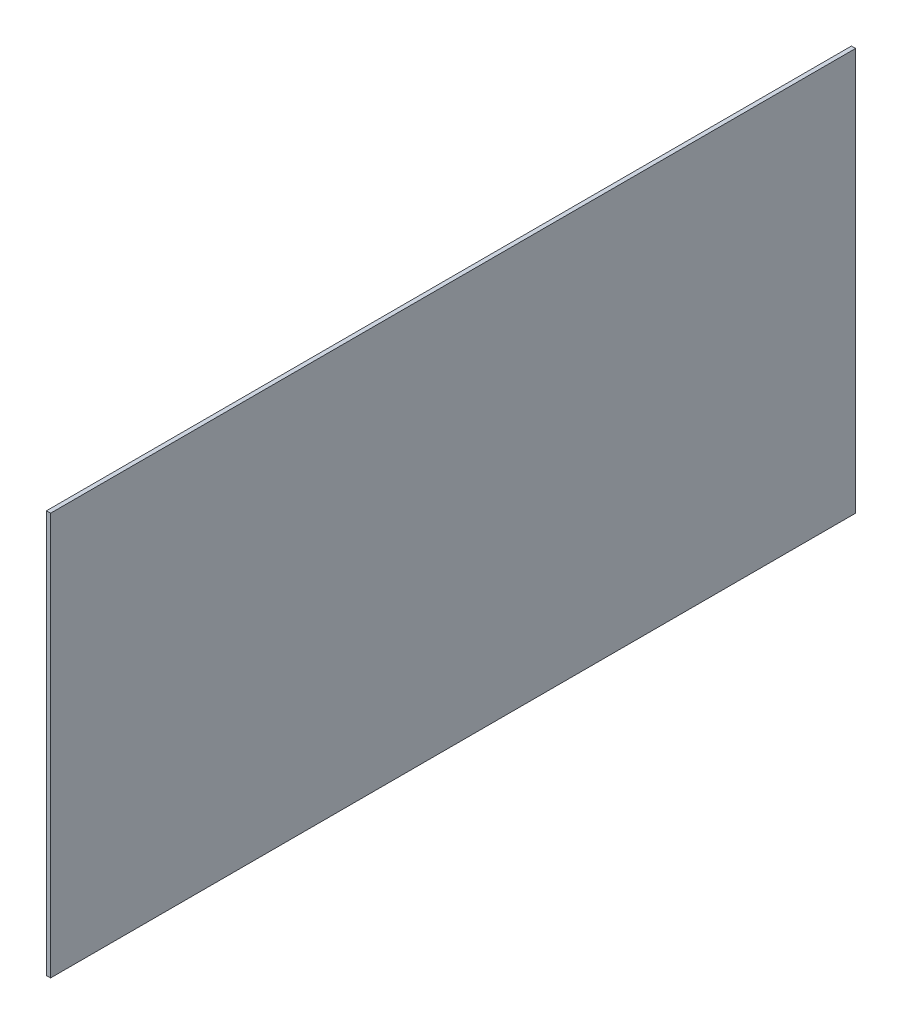
SolidWorks part; units mm, degrees
ref_plane "Front" through (0, 0, 0) normal (0, 0, 1) x (1, 0, 0)
ref_plane "Top" through (0, 0, 0) normal (0, 1, 0) x (1, 0, 0)
ref_plane "Right" through (0, 0, 0) normal (1, 0, 0) x (0, 0, -1)
sketch "Sketch1" plane through (0, 0, 0) normal (1, 0, 0) x (0, 0, -1)
  line L1 (-133.9606, 24.039) -> (446.0394, 24.039)
  line L2 (-133.9606, 24.039) -> (-133.9606, -265.961)
  line L3 (-133.9606, -265.961) -> (446.0394, -265.961)
  line L4 (446.0394, 24.039) -> (446.0394, -265.961)
  dimension "D1" = 290
  dimension "D2" = 580
extrude "Boss-Extrude1" add sketch "Sketch1" along normal blind 3
sketch "Sketch2" plane through (3, 0, 0) normal (1, 0, 0) x (0, 0, -1)
  line L0 (86.5939, -170.6598) -> (82.6976, -168.8352)
  line L1 (82.6976, -168.8352) -> (71.0139, -163.3632)
  line L2 (71.0139, -163.3632) -> (57.3791, -156.9784)
  line L3 (57.3791, -156.9784) -> (45.5604, -151.4443)
  line L4 (45.5604, -151.4443) -> (35.4261, -146.6985)
  line L5 (35.4261, -146.6985) -> (26.8483, -142.6815)
  line L6 (26.8483, -142.6815) -> (19.6976, -139.3311)
  line L7 (19.6976, -139.3311) -> (13.8418, -136.5888)
  line L8 (13.8418, -136.5888) -> (9.1524, -134.3944)
  line L9 (9.1524, -134.3944) -> (5.5002, -132.6839)
  line L10 (5.5002, -132.6839) -> (2.7568, -131.3991)
  line L11 (2.7568, -131.3991) -> (0.7899, -130.4769)
  line L12 (0.7899, -130.4769) -> (-0.5281, -129.8611)
  line L13 (-0.5281, -129.8611) -> (-1.3276, -129.4865)
  line L14 (-1.3276, -129.4865) -> (-1.7383, -129.2939)
  line L15 (-1.7383, -129.2939) -> (-1.8887, -129.2229)
  line L16 (-1.8887, -129.2229) -> (-1.9099, -129.2136)
  line L17 (-26.9111, -208.381) -> (86.5939, -170.6598)
  line L18 (86.5939, -170.6598) -> (183.0985, -202.7924)
  line L19 (173.0993, -107.7912) -> (86.5939, -170.6598)
  line L20 (183.0985, -202.7924) -> (299.9586, -173.7778)
  line L21 (173.0993, -107.7912) -> (300.7804, -173.7778)
  line L22 (200.6985, -262.8655) -> (182.9979, -202.8441)
  line L23 (323.0293, -263.2886) -> (301.6386, -177.8001)
  line L24 (301.6386, -177.8001) -> (300.6491, -173.846)
  line L25 (183.0985, -202.7924) -> (173.0993, -107.7912)
  line L26 (125.9767, -263.8437) -> (183.0985, -202.7924)
  line L27 (39.8988, -263.8649) -> (-26.9111, -208.381)
  line L28 (-26.9111, -208.381) -> (-26.0591, -166.4437)
  line L29 (-26.0591, -166.4437) -> (-1.9099, -129.2136)
  line L30 (110.9929, -175.8464) -> (110.9929, -176.4773)
  line L31 (110.9929, -176.4773) -> (110.4836, -178.3701)
  line L32 (110.4836, -178.3701) -> (109.0929, -180.4298)
  line L33 (109.0929, -180.4298) -> (107.0318, -181.8205)
  line L34 (107.0318, -181.8205) -> (105.139, -182.3301)
  line L35 (105.139, -182.3301) -> (104.5081, -182.3301)
  line L36 (104.5081, -182.3301) -> (103.8755, -182.3301)
  line L37 (103.8755, -182.3301) -> (101.9827, -181.8205)
  line L38 (101.9827, -181.8205) -> (99.9236, -180.4298)
  line L39 (99.9236, -180.4298) -> (98.5329, -178.3701)
  line L40 (98.5329, -178.3701) -> (98.0247, -176.4773)
  line L41 (98.0247, -176.4773) -> (98.0247, -175.8464)
  line L42 (98.0247, -175.8464) -> (98.0247, -175.2144)
  line L43 (98.0247, -175.2144) -> (98.5329, -173.3216)
  line L44 (98.5329, -173.3216) -> (99.9236, -171.2619)
  line L45 (99.9236, -171.2619) -> (101.9827, -169.8712)
  line L46 (101.9827, -169.8712) -> (103.8755, -169.363)
  line L47 (103.8755, -169.363) -> (104.5081, -169.363)
  line L48 (104.5081, -169.363) -> (105.139, -169.363)
  line L49 (105.139, -169.363) -> (107.0318, -169.8712)
  line L50 (107.0318, -169.8712) -> (109.0929, -171.2619)
  line L51 (109.0929, -171.2619) -> (110.4836, -173.3216)
  line L52 (110.4836, -173.3216) -> (110.9929, -175.2144)
  line L53 (110.9929, -175.2144) -> (110.9929, -175.8464)
  line L54 (127.6708, -182.6407) -> (127.6708, -183.2716)
  line L55 (127.6708, -183.2716) -> (127.162, -185.1644)
  line L56 (127.162, -185.1644) -> (125.7699, -187.2241)
  line L57 (125.7699, -187.2241) -> (123.7096, -188.6148)
  line L58 (123.7096, -188.6148) -> (121.8171, -189.1247)
  line L59 (121.8171, -189.1247) -> (121.1854, -189.1247)
  line L60 (121.1854, -189.1247) -> (120.5536, -189.1247)
  line L61 (120.5536, -189.1247) -> (118.6611, -188.6148)
  line L62 (118.6611, -188.6148) -> (116.6017, -187.2241)
  line L63 (116.6017, -187.2241) -> (115.211, -185.1644)
  line L64 (115.211, -185.1644) -> (114.7028, -183.2716)
  line L65 (114.7028, -183.2716) -> (114.7028, -182.6407)
  line L66 (114.7028, -182.6407) -> (114.7028, -182.0087)
  line L67 (114.7028, -182.0087) -> (115.211, -180.1159)
  line L68 (115.211, -180.1159) -> (116.6017, -178.0562)
  line L69 (116.6017, -178.0562) -> (118.6611, -176.6655)
  line L70 (118.6611, -176.6655) -> (120.5536, -176.1573)
  line L71 (120.5536, -176.1573) -> (121.1854, -176.1573)
  line L72 (121.1854, -176.1573) -> (121.8171, -176.1573)
  line L73 (121.8171, -176.1573) -> (123.7096, -176.6655)
  line L74 (123.7096, -176.6655) -> (125.7699, -178.0562)
  line L75 (125.7699, -178.0562) -> (127.162, -180.1159)
  line L76 (127.162, -180.1159) -> (127.6708, -182.0087)
  line L77 (127.6708, -182.0087) -> (127.6708, -182.6407)
  line L78 (145.1729, -187.171) -> (145.1729, -187.8019)
  line L79 (145.1729, -187.8019) -> (144.6642, -189.6947)
  line L80 (144.6642, -189.6947) -> (143.272, -191.7544)
  line L81 (143.272, -191.7544) -> (141.2118, -193.1451)
  line L82 (141.2118, -193.1451) -> (139.3193, -193.6547)
  line L83 (139.3193, -193.6547) -> (138.6875, -193.6547)
  line L84 (138.6875, -193.6547) -> (138.0558, -193.6547)
  line L85 (138.0558, -193.6547) -> (136.1633, -193.1451)
  line L86 (136.1633, -193.1451) -> (134.103, -191.7544)
  line L87 (134.103, -191.7544) -> (132.7137, -189.6947)
  line L88 (132.7137, -189.6947) -> (132.2049, -187.8019)
  line L89 (132.2049, -187.8019) -> (132.2049, -187.171)
  line L90 (132.2049, -187.171) -> (132.2049, -186.5389)
  line L91 (132.2049, -186.5389) -> (132.7137, -184.6461)
  line L92 (132.7137, -184.6461) -> (134.103, -182.5865)
  line L93 (134.103, -182.5865) -> (136.1633, -181.1957)
  line L94 (136.1633, -181.1957) -> (138.0558, -180.6875)
  line L95 (138.0558, -180.6875) -> (138.6875, -180.6875)
  line L96 (138.6875, -180.6875) -> (139.3193, -180.6875)
  line L97 (139.3193, -180.6875) -> (141.2118, -181.1957)
  line L98 (141.2118, -181.1957) -> (143.272, -182.5865)
  line L99 (143.272, -182.5865) -> (144.6642, -184.6461)
  line L100 (144.6642, -184.6461) -> (145.1729, -186.5389)
  line L101 (145.1729, -186.5389) -> (145.1729, -187.171)
  line L102 (165.9681, -194.1718) -> (165.9681, -194.8028)
  line L103 (165.9681, -194.8028) -> (165.4594, -196.6956)
  line L104 (165.4594, -196.6956) -> (164.0672, -198.755)
  line L105 (164.0672, -198.755) -> (162.0098, -200.1457)
  line L106 (162.0098, -200.1457) -> (160.1173, -200.6553)
  line L107 (160.1173, -200.6553) -> (159.4855, -200.6553)
  line L108 (159.4855, -200.6553) -> (158.8538, -200.6553)
  line L109 (158.8538, -200.6553) -> (156.9612, -200.1457)
  line L110 (156.9612, -200.1457) -> (154.8982, -198.755)
  line L111 (154.8982, -198.755) -> (153.5089, -196.6956)
  line L112 (153.5089, -196.6956) -> (153.0001, -194.8028)
  line L113 (153.0001, -194.8028) -> (153.0001, -194.1718)
  line L114 (153.0001, -194.1718) -> (153.0001, -193.5395)
  line L115 (153.0001, -193.5395) -> (153.5089, -191.6467)
  line L116 (153.5089, -191.6467) -> (154.8982, -189.5871)
  line L117 (154.8982, -189.5871) -> (156.9612, -188.1963)
  line L118 (156.9612, -188.1963) -> (158.8538, -187.6881)
  line L119 (158.8538, -187.6881) -> (159.4855, -187.6881)
  line L120 (159.4855, -187.6881) -> (160.1173, -187.6881)
  line L121 (160.1173, -187.6881) -> (162.0098, -188.1963)
  line L122 (162.0098, -188.1963) -> (164.0672, -189.5871)
  line L123 (164.0672, -189.5871) -> (165.4594, -191.6467)
  line L124 (165.4594, -191.6467) -> (165.9681, -193.5395)
  line L125 (165.9681, -193.5395) -> (165.9681, -194.1718)
  line L126 (4.7935, -128.9573) -> (4.7935, -129.5835)
  line L127 (4.7935, -129.5835) -> (4.287, -131.4628)
  line L128 (4.287, -131.4628) -> (2.9072, -133.5088)
  line L129 (2.9072, -133.5088) -> (0.8609, -134.8886)
  line L130 (0.8609, -134.8886) -> (-1.0182, -135.3955)
  line L131 (-1.0182, -135.3955) -> (-1.6444, -135.3955)
  line L132 (-1.6444, -135.3955) -> (-2.2722, -135.3955)
  line L133 (-2.2722, -135.3955) -> (-4.1513, -134.8886)
  line L134 (-4.1513, -134.8886) -> (-6.1976, -133.5088)
  line L135 (-6.1976, -133.5088) -> (-7.5774, -131.4628)
  line L136 (-7.5774, -131.4628) -> (-8.0825, -129.5835)
  line L137 (-8.0825, -129.5835) -> (-8.0825, -128.9573)
  line L138 (-8.0825, -128.9573) -> (-8.0825, -128.3294)
  line L139 (-8.0825, -128.3294) -> (-7.5774, -126.4504)
  line L140 (-7.5774, -126.4504) -> (-6.1976, -124.4044)
  line L141 (-6.1976, -124.4044) -> (-4.1513, -123.0243)
  line L142 (-4.1513, -123.0243) -> (-2.2722, -122.5194)
  line L143 (-2.2722, -122.5194) -> (-1.6444, -122.5194)
  line L144 (-1.6444, -122.5194) -> (-1.0182, -122.5194)
  line L145 (-1.0182, -122.5194) -> (0.8609, -123.0243)
  line L146 (0.8609, -123.0243) -> (2.9072, -124.4044)
  line L147 (2.9072, -124.4044) -> (4.287, -126.4504)
  line L148 (4.287, -126.4504) -> (4.7935, -128.3294)
  line L149 (4.7935, -128.3294) -> (4.7935, -128.9573)
  line L150 (-4.4714, -143.7823) -> (-4.4714, -144.4088)
  line L151 (-4.4714, -144.4088) -> (-4.9779, -146.2878)
  line L152 (-4.9779, -146.2878) -> (-6.3583, -148.3335)
  line L153 (-6.3583, -148.3335) -> (-8.404, -149.7136)
  line L154 (-8.404, -149.7136) -> (-10.2831, -150.2204)
  line L155 (-10.2831, -150.2204) -> (-10.9092, -150.2204)
  line L156 (-10.9092, -150.2204) -> (-11.5371, -150.2204)
  line L157 (-11.5371, -150.2204) -> (-13.4162, -149.7136)
  line L158 (-13.4162, -149.7136) -> (-15.4624, -148.3335)
  line L159 (-15.4624, -148.3335) -> (-16.8425, -146.2878)
  line L160 (-16.8425, -146.2878) -> (-17.3474, -144.4088)
  line L161 (-17.3474, -144.4088) -> (-17.3474, -143.7823)
  line L162 (-17.3474, -143.7823) -> (-17.3474, -143.1542)
  line L163 (-17.3474, -143.1542) -> (-16.8425, -141.2754)
  line L164 (-16.8425, -141.2754) -> (-15.4624, -139.2294)
  line L165 (-15.4624, -139.2294) -> (-13.4162, -137.849)
  line L166 (-13.4162, -137.849) -> (-11.5371, -137.3444)
  line L167 (-11.5371, -137.3444) -> (-10.9092, -137.3444)
  line L168 (-10.9092, -137.3444) -> (-10.2831, -137.3444)
  line L169 (-10.2831, -137.3444) -> (-8.404, -137.849)
  line L170 (-8.404, -137.849) -> (-6.3583, -139.2294)
  line L171 (-6.3583, -139.2294) -> (-4.9779, -141.2754)
  line L172 (-4.9779, -141.2754) -> (-4.4714, -143.1542)
  line L173 (-4.4714, -143.1542) -> (-4.4714, -143.7823)
  line L174 (-14.3552, -158.401) -> (-14.3552, -159.0272)
  line L175 (-14.3552, -159.0272) -> (-14.8617, -160.9063)
  line L176 (-14.8617, -160.9063) -> (-16.2421, -162.9536)
  line L177 (-16.2421, -162.9536) -> (-18.2878, -164.334)
  line L178 (-18.2878, -164.334) -> (-20.1669, -164.8405)
  line L179 (-20.1669, -164.8405) -> (-20.793, -164.8405)
  line L180 (-20.793, -164.8405) -> (-21.4212, -164.8405)
  line L181 (-21.4212, -164.8405) -> (-23.3, -164.334)
  line L182 (-23.3, -164.334) -> (-25.3462, -162.9536)
  line L183 (-25.3462, -162.9536) -> (-26.7263, -160.9063)
  line L184 (-26.7263, -160.9063) -> (-27.2312, -159.0272)
  line L185 (-27.2312, -159.0272) -> (-27.2312, -158.401)
  line L186 (-27.2312, -158.401) -> (-27.2312, -157.7731)
  line L187 (-27.2312, -157.7731) -> (-26.7263, -155.894)
  line L188 (-26.7263, -155.894) -> (-25.3462, -153.8478)
  line L189 (-25.3462, -153.8478) -> (-23.3, -152.468)
  line L190 (-23.3, -152.468) -> (-21.4212, -151.9628)
  line L191 (-21.4212, -151.9628) -> (-20.793, -151.9628)
  line L192 (-20.793, -151.9628) -> (-20.1669, -151.9628)
  line L193 (-20.1669, -151.9628) -> (-18.2878, -152.468)
  line L194 (-18.2878, -152.468) -> (-16.2421, -153.8478)
  line L195 (-16.2421, -153.8478) -> (-14.8617, -155.894)
  line L196 (-14.8617, -155.894) -> (-14.3552, -157.7731)
  line L197 (-14.3552, -157.7731) -> (-14.3552, -158.401)
  line L198 (-19.539, -174.2813) -> (-19.539, -174.908)
  line L199 (-19.539, -174.908) -> (-20.0458, -176.7868)
  line L200 (-20.0458, -176.7868) -> (-21.4257, -178.8328)
  line L201 (-21.4257, -178.8328) -> (-23.4716, -180.2132)
  line L202 (-23.4716, -180.2132) -> (-25.3507, -180.7194)
  line L203 (-25.3507, -180.7194) -> (-25.9772, -180.7194)
  line L204 (-25.9772, -180.7194) -> (-26.605, -180.7194)
  line L205 (-26.605, -180.7194) -> (-28.4841, -180.2132)
  line L206 (-28.4841, -180.2132) -> (-30.5298, -178.8328)
  line L207 (-30.5298, -178.8328) -> (-31.9099, -176.7868)
  line L208 (-31.9099, -176.7868) -> (-32.415, -174.908)
  line L209 (-32.415, -174.908) -> (-32.415, -174.2813)
  line L210 (-32.415, -174.2813) -> (-32.415, -173.6534)
  line L211 (-32.415, -173.6534) -> (-31.9099, -171.7743)
  line L212 (-31.9099, -171.7743) -> (-30.5298, -169.7286)
  line L213 (-30.5298, -169.7286) -> (-28.4841, -168.3485)
  line L214 (-28.4841, -168.3485) -> (-26.605, -167.8434)
  line L215 (-26.605, -167.8434) -> (-25.9772, -167.8434)
  line L216 (-25.9772, -167.8434) -> (-25.3507, -167.8434)
  line L217 (-25.3507, -167.8434) -> (-23.4716, -168.3485)
  line L218 (-23.4716, -168.3485) -> (-21.4257, -169.7286)
  line L219 (-21.4257, -169.7286) -> (-20.0458, -171.7743)
  line L220 (-20.0458, -171.7743) -> (-19.539, -173.6534)
  line L221 (-19.539, -173.6534) -> (-19.539, -174.2813)
  line L222 (-20.2549, -190.0754) -> (-20.2549, -190.7019)
  line L223 (-20.2549, -190.7019) -> (-20.7612, -192.581)
  line L224 (-20.7612, -192.581) -> (-22.1416, -194.6269)
  line L225 (-22.1416, -194.6269) -> (-24.1889, -196.0068)
  line L226 (-24.1889, -196.0068) -> (-26.068, -196.5136)
  line L227 (-26.068, -196.5136) -> (-26.6945, -196.5136)
  line L228 (-26.6945, -196.5136) -> (-27.3223, -196.5136)
  line L229 (-27.3223, -196.5136) -> (-29.2014, -196.0068)
  line L230 (-29.2014, -196.0068) -> (-31.2474, -194.6269)
  line L231 (-31.2474, -194.6269) -> (-32.6275, -192.581)
  line L232 (-32.6275, -192.581) -> (-33.1326, -190.7019)
  line L233 (-33.1326, -190.7019) -> (-33.1326, -190.0754)
  line L234 (-33.1326, -190.0754) -> (-33.1326, -189.4476)
  line L235 (-33.1326, -189.4476) -> (-32.6275, -187.5685)
  line L236 (-32.6275, -187.5685) -> (-31.2474, -185.5225)
  line L237 (-31.2474, -185.5225) -> (-29.2014, -184.1427)
  line L238 (-29.2014, -184.1427) -> (-27.3223, -183.6376)
  line L239 (-27.3223, -183.6376) -> (-26.6945, -183.6376)
  line L240 (-26.6945, -183.6376) -> (-26.068, -183.6376)
  line L241 (-26.068, -183.6376) -> (-24.1889, -184.1427)
  line L242 (-24.1889, -184.1427) -> (-22.1416, -185.5225)
  line L243 (-22.1416, -185.5225) -> (-20.7612, -187.5685)
  line L244 (-20.7612, -187.5685) -> (-20.2549, -189.4476)
  line L245 (-20.2549, -189.4476) -> (-20.2549, -190.0754)
  line L246 (119.9945, -261.4702) -> (120.0085, -260.8393)
  line L247 (120.0085, -260.8393) -> (120.5592, -258.9571)
  line L248 (120.5592, -258.9571) -> (121.996, -256.9279)
  line L249 (121.996, -256.9279) -> (124.087, -255.5842)
  line L250 (124.087, -255.5842) -> (125.9907, -255.1171)
  line L251 (125.9907, -255.1171) -> (126.6225, -255.1307)
  line L252 (126.6225, -255.1307) -> (126.9383, -255.1368)
  line L253 (126.9383, -255.1368) -> (127.8888, -255.2839)
  line L254 (127.8888, -255.2839) -> (129.0908, -255.6782)
  line L255 (129.0908, -255.6782) -> (130.1922, -256.2985)
  line L256 (130.1922, -256.2985) -> (130.9442, -256.9006)
  line L257 (130.9442, -256.9006) -> (131.165, -257.1312)
  line L258 (131.165, -257.1312) -> (131.3831, -257.3602)
  line L259 (131.3831, -257.3602) -> (131.9506, -258.1352)
  line L260 (131.9506, -258.1352) -> (132.5208, -259.2635)
  line L261 (132.5208, -259.2635) -> (132.8619, -260.4829)
  line L262 (132.8619, -260.4829) -> (132.9681, -261.4383)
  line L263 (132.9681, -261.4383) -> (132.9625, -261.7568)
  line L264 (132.9625, -261.7568) -> (132.9541, -262.0738)
  line L265 (132.9541, -262.0738) -> (132.806, -263.0247)
  line L266 (132.806, -263.0247) -> (132.4118, -264.2259)
  line L267 (132.4118, -264.2259) -> (131.7912, -265.3285)
  line L268 (131.7912, -265.3285) -> (131.1902, -266.0792)
  line L269 (131.1902, -266.0792) -> (130.961, -266.2991)
  line L270 (130.961, -266.2991) -> (130.7317, -266.5175)
  line L271 (130.7317, -266.5175) -> (129.9546, -267.0862)
  line L272 (129.9546, -267.0862) -> (128.8281, -267.6565)
  line L273 (128.8281, -267.6565) -> (127.6065, -267.9977)
  line L274 (127.6065, -267.9977) -> (126.6532, -268.1024)
  line L275 (126.6532, -268.1024) -> (126.3345, -268.0963)
  line L276 (126.3345, -268.0963) -> (126.0159, -268.0887)
  line L277 (126.0159, -268.0887) -> (125.0682, -267.9416)
  line L278 (125.0682, -267.9416) -> (123.8662, -267.5473)
  line L279 (123.8662, -267.5473) -> (122.762, -266.927)
  line L280 (122.762, -266.927) -> (122.01, -266.3249)
  line L281 (122.01, -266.3249) -> (121.792, -266.0959)
  line L282 (121.792, -266.0959) -> (121.5739, -265.8654)
  line L283 (121.5739, -265.8654) -> (121.0065, -265.0904)
  line L284 (121.0065, -265.0904) -> (120.4334, -263.962)
  line L285 (120.4334, -263.962) -> (120.0923, -262.7426)
  line L286 (120.0923, -262.7426) -> (119.9889, -261.7872)
  line L287 (119.9889, -261.7872) -> (119.9945, -261.4702)
  line L288 (196.0078, -263.005) -> (195.9715, -262.3741)
  line L289 (195.9715, -262.3741) -> (196.3684, -260.4556)
  line L290 (196.3684, -260.4556) -> (197.6347, -258.3157)
  line L291 (197.6347, -258.3157) -> (199.6111, -256.8081)
  line L292 (199.6111, -256.8081) -> (201.4701, -256.1878)
  line L293 (201.4701, -256.1878) -> (202.1018, -256.1514)
  line L294 (202.1018, -256.1514) -> (202.4177, -256.1332)
  line L295 (202.4177, -256.1332) -> (203.3765, -256.2015)
  line L296 (203.3765, -256.2015) -> (204.6065, -256.4987)
  line L297 (204.6065, -256.4987) -> (205.7555, -257.028)
  line L298 (205.7555, -257.028) -> (206.5521, -257.5679)
  line L299 (206.5521, -257.5679) -> (206.7898, -257.7787)
  line L300 (206.7898, -257.7787) -> (207.0274, -257.9896)
  line L301 (207.0274, -257.9896) -> (207.6563, -258.716)
  line L302 (207.6563, -258.716) -> (208.3161, -259.7943)
  line L303 (208.3161, -259.7943) -> (208.7549, -260.9819)
  line L304 (208.7549, -260.9819) -> (208.9366, -261.9267)
  line L305 (208.9366, -261.9267) -> (208.9534, -262.2437)
  line L306 (208.9534, -262.2437) -> (208.973, -262.5607)
  line L307 (208.973, -262.5607) -> (208.9031, -263.5192)
  line L308 (208.9031, -263.5192) -> (208.6068, -264.7491)
  line L309 (208.6068, -264.7491) -> (208.0785, -265.8987)
  line L310 (208.0785, -265.8987) -> (207.5389, -266.695)
  line L311 (207.5389, -266.695) -> (207.3293, -266.9331)
  line L312 (207.3293, -266.9331) -> (207.1168, -267.1697)
  line L313 (207.1168, -267.1697) -> (206.3872, -267.799)
  line L314 (206.3872, -267.799) -> (205.311, -268.4588)
  line L315 (205.311, -268.4588) -> (204.1229, -268.8971)
  line L316 (204.1229, -268.8971) -> (203.1781, -269.0791)
  line L317 (203.1781, -269.0791) -> (202.8622, -269.0972)
  line L318 (202.8622, -269.0972) -> (202.5435, -269.1155)
  line L319 (202.5435, -269.1155) -> (201.5847, -269.0457)
  line L320 (201.5847, -269.0457) -> (200.3547, -268.75)
  line L321 (200.3547, -268.75) -> (199.2058, -268.2207)
  line L322 (199.2058, -268.2207) -> (198.4119, -267.6823)
  line L323 (198.4119, -267.6823) -> (198.1742, -267.4715)
  line L324 (198.1742, -267.4715) -> (197.9366, -267.2591)
  line L325 (197.9366, -267.2591) -> (197.3077, -266.5311)
  line L326 (197.3077, -266.5311) -> (196.6479, -265.4528)
  line L327 (196.6479, -265.4528) -> (196.2091, -264.2653)
  line L328 (196.2091, -264.2653) -> (196.0274, -263.3205)
  line L329 (196.0274, -263.3205) -> (196.0078, -263.005)
  line L330 (154.7836, -237.7503) -> (154.7836, -238.3767)
  line L331 (154.7836, -238.3767) -> (154.2776, -240.2558)
  line L332 (154.2776, -240.2558) -> (152.8967, -242.3017)
  line L333 (152.8967, -242.3017) -> (150.8504, -243.6818)
  line L334 (150.8504, -243.6818) -> (148.9719, -244.1883)
  line L335 (148.9719, -244.1883) -> (148.3457, -244.1883)
  line L336 (148.3457, -244.1883) -> (147.7168, -244.1883)
  line L337 (147.7168, -244.1883) -> (145.8382, -243.6818)
  line L338 (145.8382, -243.6818) -> (143.792, -242.3017)
  line L339 (143.792, -242.3017) -> (142.4138, -240.2558)
  line L340 (142.4138, -240.2558) -> (141.9079, -238.3767)
  line L341 (141.9079, -238.3767) -> (141.9079, -237.7503)
  line L342 (141.9079, -237.7503) -> (141.9079, -237.1224)
  line L343 (141.9079, -237.1224) -> (142.4138, -235.2434)
  line L344 (142.4138, -235.2434) -> (143.792, -233.196)
  line L345 (143.792, -233.196) -> (145.8382, -231.8156)
  line L346 (145.8382, -231.8156) -> (147.7168, -231.3108)
  line L347 (147.7168, -231.3108) -> (148.3457, -231.3108)
  line L348 (148.3457, -231.3108) -> (148.9719, -231.3108)
  line L349 (148.9719, -231.3108) -> (150.8504, -231.8156)
  line L350 (150.8504, -231.8156) -> (152.8967, -233.196)
  line L351 (152.8967, -233.196) -> (154.2776, -235.2434)
  line L352 (154.2776, -235.2434) -> (154.7836, -237.1224)
  line L353 (154.7836, -237.1224) -> (154.7836, -237.7503)
  line L354 (126.5861, -262.6805) -> (128.7805, -261.499)
  line L355 (-17.7586, -262.9762) -> (-17.7329, -265.0343)
  line L356 (421.8337, -263.2917) -> (421.8337, -263.2264)
  line L357 (421.8337, -263.2264) -> (421.6827, -262.7017)
  line L358 (421.6827, -262.7017) -> (421.652, -262.6638)
  line L359 (421.652, -262.6638) -> (421.5597, -262.55)
  line L360 (421.5597, -262.55) -> (421.1013, -262.2452)
  line L361 (421.1013, -262.2452) -> (420.0949, -261.7159)
  line L362 (420.0949, -261.7159) -> (418.7727, -261.1396)
  line L363 (418.7727, -261.1396) -> (417.6545, -260.7134)
  line L364 (417.6545, -260.7134) -> (417.2799, -260.586)
  line L365 (417.2799, -260.586) -> (416.4916, -260.3191)
  line L366 (416.4916, -260.3191) -> (414.1518, -259.4653)
  line L367 (414.1518, -259.4653) -> (411.5381, -258.3627)
  line L368 (411.5381, -258.3627) -> (409.3129, -257.1812)
  line L369 (409.3129, -257.1812) -> (407.3617, -255.8269)
  line L370 (407.3617, -255.8269) -> (405.5615, -254.2041)
  line L371 (405.5615, -254.2041) -> (403.7976, -252.2188)
  line L372 (403.7976, -252.2188) -> (401.9442, -249.7771)
  line L373 (401.9442, -249.7771) -> (400.3871, -247.5386)
  line L374 (400.3871, -247.5386) -> (399.884, -246.7833)
  line L375 (399.884, -246.7833) -> (399.5373, -246.2601)
  line L376 (399.5373, -246.2601) -> (398.4415, -244.7268)
  line L377 (398.4415, -244.7268) -> (396.9739, -242.8188)
  line L378 (396.9739, -242.8188) -> (395.6545, -241.2719)
  line L379 (395.6545, -241.2719) -> (394.9165, -240.5045)
  line L380 (394.9165, -240.5045) -> (394.6565, -240.2997)
  line L381 (394.6565, -240.2997) -> (394.3993, -240.0996)
  line L382 (394.3993, -240.0996) -> (393.5607, -239.59)
  line L383 (393.5607, -239.59) -> (391.8471, -238.6527)
  line L384 (391.8471, -238.6527) -> (389.6275, -237.5486)
  line L385 (389.6275, -237.5486) -> (387.0502, -236.3368)
  line L386 (387.0502, -236.3368) -> (384.2435, -235.0796)
  line L387 (384.2435, -235.0796) -> (381.3307, -233.8376)
  line L388 (381.3307, -233.8376) -> (378.4598, -232.6683)
  line L389 (378.4598, -232.6683) -> (376.4275, -231.8855)
  line L390 (376.4275, -231.8855) -> (375.7482, -231.6367)
  line L391 (375.7482, -231.6367) -> (375.178, -231.4276)
  line L392 (375.178, -231.4276) -> (373.4308, -230.9043)
  line L393 (373.4308, -230.9043) -> (370.8814, -230.3947)
  line L394 (370.8814, -230.3947) -> (367.5632, -230.0277)
  line L395 (367.5632, -230.0277) -> (364.1081, -229.7881)
  line L396 (364.1081, -229.7881) -> (362.9564, -229.7258)
  line L397 (362.9564, -229.7258) -> (362.0199, -229.6743)
  line L398 (362.0199, -229.6743) -> (359.2133, -229.5044)
  line L399 (359.2133, -229.5044) -> (355.596, -229.2679)
  line L400 (355.596, -229.2679) -> (352.521, -229.042)
  line L401 (352.521, -229.042) -> (350.8997, -228.9084)
  line L402 (350.8997, -228.9084) -> (350.3993, -228.857)
  line L403 (350.3993, -228.857) -> (349.9101, -228.8052)
  line L404 (349.9101, -228.8052) -> (348.4341, -228.7113)
  line L405 (348.4341, -228.7113) -> (346.9246, -228.7751)
  line L406 (346.9246, -228.7751) -> (345.5688, -229.089)
  line L407 (345.5688, -229.089) -> (344.4394, -229.5242)
  line L408 (344.4394, -229.5242) -> (344.0704, -229.6911)
  line L409 (344.0704, -229.6911) -> (343.7797, -229.8231)
  line L410 (343.7797, -229.8231) -> (342.8796, -230.1627)
  line L411 (342.8796, -230.1627) -> (341.6133, -230.5479)
  line L412 (341.6133, -230.5479) -> (340.4224, -230.8087)
  line L413 (340.4224, -230.8087) -> (339.6956, -230.9057)
  line L414 (339.6956, -230.9057) -> (339.4552, -230.9057)
  line L415 (339.4552, -230.9057) -> (337.5096, -230.9057)
  line L416 (337.5096, -230.9057) -> (337.8674, -228.6065)
  line L417 (337.8674, -228.6065) -> (337.9401, -228.1106)
  line L418 (337.9401, -228.1106) -> (337.9457, -226.591)
  line L419 (337.9457, -226.591) -> (337.3195, -224.68)
  line L420 (337.3195, -224.68) -> (335.7401, -222.3962)
  line L421 (335.7401, -222.3962) -> (333.677, -220.0301)
  line L422 (333.677, -220.0301) -> (332.9642, -219.2658)
  line L423 (332.9642, -219.2658) -> (332.6986, -218.9821)
  line L424 (332.6986, -218.9821) -> (331.9159, -218.1253)
  line L425 (331.9159, -218.1253) -> (331.0829, -217.1746)
  line L426 (331.0829, -217.1746) -> (330.4427, -216.3734)
  line L427 (330.4427, -216.3734) -> (329.9703, -215.6883)
  line L428 (329.9703, -215.6883) -> (329.6432, -215.0766)
  line L429 (329.6432, -215.0766) -> (329.442, -214.5022)
  line L430 (329.442, -214.5022) -> (329.3357, -213.9274)
  line L431 (329.3357, -213.9274) -> (329.305, -213.4662)
  line L432 (329.305, -213.4662) -> (329.305, -213.313)
  line L433 (329.305, -213.313) -> (329.305, -212.7368)
  line L434 (329.305, -212.7368) -> (329.7131, -211.0109)
  line L435 (329.7131, -211.0109) -> (330.9906, -208.5082)
  line L436 (330.9906, -208.5082) -> (333.1934, -205.6996)
  line L437 (333.1934, -205.6996) -> (335.5723, -203.2489)
  line L438 (335.5723, -203.2489) -> (336.4026, -202.4768)
  line L439 (336.4026, -202.4768) -> (337.4006, -201.5504)
  line L440 (337.4006, -201.5504) -> (340.1624, -198.5274)
  line L441 (340.1624, -198.5274) -> (342.8097, -194.5995)
  line L442 (342.8097, -194.5995) -> (344.4954, -190.4031)
  line L443 (344.4954, -190.4031) -> (345.2529, -186.8467)
  line L444 (345.2529, -186.8467) -> (345.3759, -185.6486)
  line L445 (345.3759, -185.6486) -> (345.429, -185.1326)
  line L446 (345.429, -185.1326) -> (345.6582, -183.592)
  line L447 (345.6582, -183.592) -> (346.0664, -181.522)
  line L448 (346.0664, -181.522) -> (346.5416, -179.6776)
  line L449 (346.5416, -179.6776) -> (346.8826, -178.634)
  line L450 (346.8826, -178.634) -> (347.0336, -178.3036)
  line L451 (347.0336, -178.3036) -> (347.1706, -177.9972)
  line L452 (347.1706, -177.9972) -> (347.5032, -177.0445)
  line L453 (347.5032, -177.0445) -> (347.8722, -175.6345)
  line L454 (347.8722, -175.6345) -> (348.1126, -174.1859)
  line L455 (348.1126, -174.1859) -> (348.2049, -173.1561)
  line L456 (348.2049, -173.1561) -> (348.2049, -172.8134)
  line L457 (348.2049, -172.8134) -> (348.2049, -172.4419)
  line L458 (348.2049, -172.4419) -> (348.2804, -171.3318)
  line L459 (348.2804, -171.3318) -> (348.518, -170.1077)
  line L460 (348.518, -170.1077) -> (348.9485, -169.02)
  line L461 (348.9485, -169.02) -> (349.4265, -168.2074)
  line L462 (349.4265, -168.2074) -> (349.6026, -167.9538)
  line L463 (349.6026, -167.9538) -> (349.8821, -167.563)
  line L464 (349.8821, -167.563) -> (350.6844, -166.3587)
  line L465 (350.6844, -166.3587) -> (351.5846, -164.7978)
  line L466 (351.5846, -164.7978) -> (352.3449, -163.1633)
  line L467 (352.3449, -163.1633) -> (352.9935, -161.3463)
  line L468 (352.9935, -161.3463) -> (353.5637, -159.2379)
  line L469 (353.5637, -159.2379) -> (354.0949, -156.731)
  line L470 (354.0949, -156.731) -> (354.6204, -153.7159)
  line L471 (354.6204, -153.7159) -> (355.0397, -150.9939)
  line L472 (355.0397, -150.9939) -> (355.1711, -150.0854)
  line L473 (355.1711, -150.0854) -> (355.322, -149.0193)
  line L474 (355.322, -149.0193) -> (355.6799, -145.8098)
  line L475 (355.6799, -145.8098) -> (355.7022, -142.7768)
  line L476 (355.7022, -142.7768) -> (355.1795, -140.3758)
  line L477 (355.1795, -140.3758) -> (354.3744, -138.5666)
  line L478 (354.3744, -138.5666) -> (354.0557, -137.9946)
  line L479 (354.0557, -137.9946) -> (353.7846, -137.5063)
  line L480 (353.7846, -137.5063) -> (352.7922, -136.1416)
  line L481 (352.7922, -136.1416) -> (351.1289, -134.5294)
  line L482 (351.1289, -134.5294) -> (348.8786, -132.9975)
  line L483 (348.8786, -132.9975) -> (346.6031, -131.7586)
  line L484 (346.6031, -131.7586) -> (345.826, -131.3823)
  line L485 (345.826, -131.3823) -> (345.1998, -131.0776)
  line L486 (345.1998, -131.0776) -> (343.2486, -130.3117)
  line L487 (343.2486, -130.3117) -> (340.8865, -129.8066)
  line L488 (340.8865, -129.8066) -> (338.4209, -129.8339)
  line L489 (338.4209, -129.8339) -> (336.2377, -130.1904)
  line L490 (336.2377, -130.1904) -> (335.522, -130.36)
  line L491 (335.522, -130.36) -> (335.2956, -130.4132)
  line L492 (335.2956, -130.4132) -> (334.6135, -130.5694)
  line L493 (334.6135, -130.5694) -> (333.8951, -130.7014)
  line L494 (333.8951, -130.7014) -> (333.308, -130.7394)
  line L495 (333.308, -130.7394) -> (332.7993, -130.6681)
  line L496 (332.7993, -130.6681) -> (332.3073, -130.4724)
  line L497 (332.3073, -130.4724) -> (331.7706, -130.1373)
  line L498 (331.7706, -130.1373) -> (331.136, -129.6458)
  line L499 (331.136, -129.6458) -> (330.5322, -129.1482)
  line L500 (330.5322, -129.1482) -> (330.3393, -128.983)
  line L501 (330.3393, -128.983) -> (330.0681, -128.7555)
  line L502 (330.0681, -128.7555) -> (329.2016, -128.1368)
  line L503 (329.2016, -128.1368) -> (327.9716, -127.4075)
  line L504 (327.9716, -127.4075) -> (326.7639, -126.8537)
  line L505 (326.7639, -126.8537) -> (325.9617, -126.5882)
  line L506 (325.9617, -126.5882) -> (325.6905, -126.5398)
  line L507 (325.6905, -126.5398) -> (325.1258, -126.4353)
  line L508 (325.1258, -126.4353) -> (323.4598, -125.912)
  line L509 (323.4598, -125.912) -> (321.4079, -124.9277)
  line L510 (321.4079, -124.9277) -> (319.7195, -123.6946)
  line L511 (319.7195, -123.6946) -> (318.797, -122.6983)
  line L512 (318.797, -122.6983) -> (318.5789, -122.3173)
  line L513 (318.5789, -122.3173) -> (318.4531, -122.1024)
  line L514 (318.4531, -122.1024) -> (318.182, -121.3985)
  line L515 (318.182, -121.3985) -> (317.7627, -120.0516)
  line L516 (317.7627, -120.0516) -> (317.3741, -118.4563)
  line L517 (317.3741, -118.4563) -> (317.1309, -117.2126)
  line L518 (317.1309, -117.2126) -> (317.0694, -116.7972)
  line L519 (317.0694, -116.7972) -> (316.9296, -115.9113)
  line L520 (316.9296, -115.9113) -> (316.3454, -113.2847)
  line L521 (316.3454, -113.2847) -> (315.3334, -110.9595)
  line L522 (315.3334, -110.9595) -> (313.7904, -109.4673)
  line L523 (313.7904, -109.4673) -> (312.0824, -108.6454)
  line L524 (312.0824, -108.6454) -> (311.4841, -108.454)
  line L525 (311.4841, -108.454) -> (311.1655, -108.3497)
  line L526 (311.1655, -108.3497) -> (310.1871, -108.0704)
  line L527 (310.1871, -108.0704) -> (308.9068, -107.752)
  line L528 (308.9068, -107.752) -> (307.7802, -107.5303)
  line L529 (307.7802, -107.5303) -> (307.168, -107.4442)
  line L530 (307.168, -107.4442) -> (306.9611, -107.4395)
  line L531 (306.9611, -107.4395) -> (306.7599, -107.4347)
  line L532 (306.7599, -107.4347) -> (305.6026, -107.6338)
  line L533 (305.6026, -107.6338) -> (302.9972, -108.1889)
  line L534 (302.9972, -108.1889) -> (299.5281, -109.0197)
  line L535 (299.5281, -109.0197) -> (296.5482, -109.7768)
  line L536 (296.5482, -109.7768) -> (295.5642, -110.0404)
  line L537 (295.5642, -110.0404) -> (294.801, -110.2422)
  line L538 (294.801, -110.2422) -> (292.5227, -110.8382)
  line L539 (292.5227, -110.8382) -> (290.0851, -111.4526)
  line L540 (290.0851, -111.4526) -> (288.1227, -111.9013)
  line L541 (288.1227, -111.9013) -> (286.5126, -112.2063)
  line L542 (286.5126, -112.2063) -> (285.1344, -112.3835)
  line L543 (285.1344, -112.3835) -> (283.8597, -112.4564)
  line L544 (283.8597, -112.4564) -> (282.5766, -112.4414)
  line L545 (282.5766, -112.4414) -> (281.5116, -112.3866)
  line L546 (281.5116, -112.3866) -> (281.1537, -112.3625)
  line L547 (281.1537, -112.3625) -> (280.6729, -112.3293)
  line L548 (280.6729, -112.3293) -> (279.2277, -112.1654)
  line L549 (279.2277, -112.1654) -> (277.3044, -111.8621)
  line L550 (277.3044, -111.8621) -> (275.602, -111.4906)
  line L551 (275.602, -111.4906) -> (274.6516, -111.2203)
  line L552 (274.6516, -111.2203) -> (274.3497, -111.0976)
  line L553 (274.3497, -111.0976) -> (274.0366, -110.9687)
  line L554 (274.0366, -110.9687) -> (273.1253, -110.5184)
  line L555 (273.1253, -110.5184) -> (272.3426, -109.8916)
  line L556 (272.3426, -109.8916) -> (271.8366, -109.0365)
  line L557 (271.8366, -109.0365) -> (271.5263, -108.0933)
  line L558 (271.5263, -108.0933) -> (271.448, -107.7747)
  line L559 (271.448, -107.7747) -> (271.3362, -107.3243)
  line L560 (271.3362, -107.3243) -> (270.9504, -105.9867)
  line L561 (270.9504, -105.9867) -> (270.3997, -104.5473)
  line L562 (270.3997, -104.5473) -> (269.7288, -103.4099)
  line L563 (269.7288, -103.4099) -> (268.8818, -102.5243)
  line L564 (268.8818, -102.5243) -> (267.8028, -101.8433)
  line L565 (267.8028, -101.8433) -> (266.4274, -101.3183)
  line L566 (266.4274, -101.3183) -> (264.6971, -100.8999)
  line L567 (264.6971, -100.8999) -> (263.0925, -100.6195)
  line L568 (263.0925, -100.6195) -> (262.5586, -100.5418)
  line L569 (262.5586, -100.5418) -> (261.7898, -100.4297)
  line L570 (261.7898, -100.4297) -> (259.5059, -100.0023)
  line L571 (259.5059, -100.0023) -> (257.633, -99.3316)
  line L572 (257.633, -99.3316) -> (256.5484, -98.3021)
  line L573 (256.5484, -98.3021) -> (255.9893, -97.1054)
  line L574 (255.9893, -97.1054) -> (255.8551, -96.69)
  line L575 (255.8551, -96.69) -> (255.7657, -96.4076)
  line L576 (255.7657, -96.4076) -> (255.4106, -95.5916)
  line L577 (255.4106, -95.5916) -> (254.6978, -94.192)
  line L578 (254.6978, -94.192) -> (253.8284, -92.6693)
  line L579 (253.8284, -92.6693) -> (253.1352, -91.5623)
  line L580 (253.1352, -91.5623) -> (252.8892, -91.2042)
  line L581 (252.8892, -91.2042) -> (250.6109, -87.8676)
  line L582 (250.6109, -87.8676) -> (250.773, -78.9029)
  line L583 (250.773, -78.9029) -> (250.938, -69.9397)
  line L584 (250.938, -69.9397) -> (249.1461, -67.1644)
  line L585 (249.1461, -67.1644) -> (248.7268, -66.5153)
  line L586 (248.7268, -66.5153) -> (247.2592, -64.7103)
  line L587 (247.2592, -64.7103) -> (245.1682, -62.7904)
  line L588 (245.1682, -62.7904) -> (243.0437, -61.5391)
  line L589 (243.0437, -61.5391) -> (241.5649, -61.0916)
  line L590 (241.5649, -61.0916) -> (241.0757, -61.0916)
  line L591 (241.0757, -61.0916) -> (240.5194, -61.0916)
  line L592 (240.5194, -61.0916) -> (238.8589, -61.659)
  line L593 (238.8589, -61.659) -> (236.754, -63.3623)
  line L594 (236.754, -63.3623) -> (234.758, -66.1969)
  line L595 (234.758, -66.1969) -> (233.2876, -69.1449)
  line L596 (233.2876, -69.1449) -> (232.8767, -70.1611)
  line L597 (232.8767, -70.1611) -> (232.5329, -71.0072)
  line L598 (232.5329, -71.0072) -> (231.4259, -73.5189)
  line L599 (231.4259, -73.5189) -> (230.1819, -75.6208)
  line L600 (230.1819, -75.6208) -> (228.7702, -76.9375)
  line L601 (228.7702, -76.9375) -> (227.3306, -77.723)
  line L602 (227.3306, -77.723) -> (226.833, -77.9385)
  line L603 (226.833, -77.9385) -> (226.1537, -78.2281)
  line L604 (226.1537, -78.2281) -> (222.8691, -78.7542)
  line L605 (222.8691, -78.7542) -> (219.5201, -78.0386)
  line L606 (219.5201, -78.0386) -> (218.8129, -77.7093)
  line L607 (218.8129, -77.7093) -> (218.483, -77.5544)
  line L608 (218.483, -77.5544) -> (217.513, -77.042)
  line L609 (217.513, -77.042) -> (216.5067, -76.3563)
  line L610 (216.5067, -76.3563) -> (215.7687, -75.5828)
  line L611 (215.7687, -75.5828) -> (215.2767, -74.6533)
  line L612 (215.2767, -74.6533) -> (214.9999, -73.4977)
  line L613 (214.9999, -73.4977) -> (214.9189, -72.051)
  line L614 (214.9189, -72.051) -> (215.0055, -70.2413)
  line L615 (215.0055, -70.2413) -> (215.1677, -68.561)
  line L616 (215.1677, -68.561) -> (215.2347, -68.003)
  line L617 (215.2347, -68.003) -> (215.313, -67.3203)
  line L618 (215.313, -67.3203) -> (215.5143, -65.2702)
  line L619 (215.5143, -65.2702) -> (215.6121, -63.3002)
  line L620 (215.6121, -63.3002) -> (215.5283, -61.9182)
  line L621 (215.5283, -61.9182) -> (215.3605, -61.1813)
  line L622 (215.3605, -61.1813) -> (215.2599, -60.9566)
  line L623 (215.2599, -60.9566) -> (215.0502, -60.4836)
  line L624 (215.0502, -60.4836) -> (213.9349, -59.2824)
  line L625 (213.9349, -59.2824) -> (211.7544, -57.9464)
  line L626 (211.7544, -57.9464) -> (209.0177, -57.0332)
  line L627 (209.0177, -57.0332) -> (206.7702, -56.6603)
  line L628 (206.7702, -56.6603) -> (206.0182, -56.6315)
  line L629 (206.0182, -56.6315) -> (205.68, -56.6178)
  line L630 (205.68, -56.6178) -> (204.0167, -56.6891)
  line L631 (204.0167, -56.6891) -> (202.4205, -56.956)
  line L632 (202.4205, -56.956) -> (202.1158, -57.0407)
  line L633 (202.1158, -57.0407) -> (201.4169, -57.2347)
  line L634 (201.4169, -57.2347) -> (199.4657, -58.3375)
  line L635 (199.4657, -58.3375) -> (196.6563, -60.6686)
  line L636 (196.6563, -60.6686) -> (193.9727, -63.7472)
  line L637 (193.9727, -63.7472) -> (192.2004, -66.3649)
  line L638 (192.2004, -66.3649) -> (191.7084, -67.2902)
  line L639 (191.7084, -67.2902) -> (191.4792, -67.7165)
  line L640 (191.4792, -67.7165) -> (190.7496, -68.9752)
  line L641 (190.7496, -68.9752) -> (189.7349, -70.584)
  line L642 (189.7349, -70.584) -> (188.7816, -71.9325)
  line L643 (188.7816, -71.9325) -> (188.2253, -72.6333)
  line L644 (188.2253, -72.6333) -> (188.0157, -72.841)
  line L645 (188.0157, -72.841) -> (187.792, -73.0594)
  line L646 (187.792, -73.0594) -> (187.0904, -73.6766)
  line L647 (187.0904, -73.6766) -> (186.2853, -74.0543)
  line L648 (186.2853, -74.0543) -> (185.2454, -74.0481)
  line L649 (185.2454, -74.0481) -> (184.021, -73.8175)
  line L650 (184.021, -73.8175) -> (183.6157, -73.7297)
  line L651 (183.6157, -73.7297) -> (183.2439, -73.6478)
  line L652 (183.2439, -73.6478) -> (182.1145, -73.484)
  line L653 (182.1145, -73.484) -> (180.1353, -73.2836)
  line L654 (180.1353, -73.2836) -> (177.9381, -73.1474)
  line L655 (177.9381, -73.1474) -> (176.3196, -73.0988)
  line L656 (176.3196, -73.0988) -> (175.7801, -73.0988)
  line L657 (175.7801, -73.0988) -> (170.8014, -73.0988)
  line L658 (170.8014, -73.0988) -> (170.8014, -71.4562)
  line L659 (170.8014, -71.4562) -> (170.8014, -71.2485)
  line L660 (170.8014, -71.2485) -> (170.8685, -70.6254)
  line L661 (170.8685, -70.6254) -> (171.0474, -69.5802)
  line L662 (171.0474, -69.5802) -> (171.313, -68.455)
  line L663 (171.313, -68.455) -> (171.545, -67.6466)
  line L664 (171.545, -67.6466) -> (171.6372, -67.3827)
  line L665 (171.6372, -67.3827) -> (171.7966, -66.9108)
  line L666 (171.7966, -66.9108) -> (172.1935, -65.4689)
  line L667 (172.1935, -65.4689) -> (172.4228, -63.9295)
  line L668 (172.4228, -63.9295) -> (172.3165, -62.7568)
  line L669 (172.3165, -62.7568) -> (171.8693, -61.9487)
  line L670 (171.8693, -61.9487) -> (171.081, -61.4983)
  line L671 (171.081, -61.4983) -> (169.9404, -61.4027)
  line L672 (169.9404, -61.4027) -> (168.4477, -61.6543)
  line L673 (168.4477, -61.6543) -> (167.05, -62.0789)
  line L674 (167.05, -62.0789) -> (166.5943, -62.2503)
  line L675 (166.5943, -62.2503) -> (166.175, -62.4082)
  line L676 (166.175, -62.4082) -> (164.9059, -62.8784)
  line L677 (164.9059, -62.8784) -> (162.7506, -63.6701)
  line L678 (162.7506, -63.6701) -> (160.3996, -64.5255)
  line L679 (160.3996, -64.5255) -> (158.7056, -65.138)
  line L680 (158.7056, -65.138) -> (158.1381, -65.3412)
  line L681 (158.1381, -65.3412) -> (157.5734, -65.543)
  line L682 (157.5734, -65.543) -> (155.9046, -66.2148)
  line L683 (155.9046, -66.2148) -> (153.945, -67.1263)
  line L684 (153.945, -67.1263) -> (152.3823, -68.0105)
  line L685 (152.3823, -68.0105) -> (151.5717, -68.5791)
  line L686 (151.5717, -68.5791) -> (151.3368, -68.8084)
  line L687 (151.3368, -68.8084) -> (150.7302, -69.4074)
  line L688 (150.7302, -69.4074) -> (149.3717, -71.6821)
  line L689 (149.3717, -71.6821) -> (148.6309, -75.2812)
  line L690 (148.6309, -75.2812) -> (149.1033, -79.6898)
  line L691 (149.1033, -79.6898) -> (150.283, -83.7013)
  line L692 (150.283, -83.7013) -> (150.7973, -84.9908)
  line L693 (150.7973, -84.9908) -> (150.993, -85.4834)
  line L694 (150.993, -85.4834) -> (151.5549, -86.9772)
  line L695 (151.5549, -86.9772) -> (152.0497, -88.5351)
  line L696 (152.0497, -88.5351) -> (152.2593, -89.7117)
  line L697 (152.2593, -89.7117) -> (152.1699, -90.5582)
  line L698 (152.1699, -90.5582) -> (151.7618, -91.1223)
  line L699 (151.7618, -91.1223) -> (151.021, -91.4558)
  line L700 (151.021, -91.4558) -> (149.928, -91.6062)
  line L701 (149.928, -91.6062) -> (148.8293, -91.6302)
  line L702 (148.8293, -91.6302) -> (148.4631, -91.6244)
  line L703 (148.4631, -91.6244) -> (148.0382, -91.6151)
  line L704 (148.0382, -91.6151) -> (146.7719, -91.4664)
  line L705 (146.7719, -91.4664) -> (144.8934, -91.0326)
  line L706 (144.8934, -91.0326) -> (142.6682, -90.2714)
  line L707 (142.6682, -90.2714) -> (140.6108, -89.4341)
  line L708 (140.6108, -89.4341) -> (139.9343, -89.137)
  line L709 (139.9343, -89.137) -> (139.3668, -88.8885)
  line L710 (139.3668, -88.8885) -> (137.6532, -88.1709)
  line L711 (137.6532, -88.1709) -> (135.5315, -87.3401)
  line L712 (135.5315, -87.3401) -> (133.8095, -86.7301)
  line L713 (133.8095, -86.7301) -> (132.9513, -86.4707)
  line L714 (132.9513, -86.4707) -> (132.7193, -86.433)
  line L715 (132.7193, -86.433) -> (132.2692, -86.3586)
  line L716 (132.2692, -86.3586) -> (130.8436, -86.6013)
  line L717 (130.8436, -86.6013) -> (128.8476, -87.7418)
  line L718 (128.8476, -87.7418) -> (126.67, -89.9013)
  line L719 (126.67, -89.9013) -> (124.811, -92.2975)
  line L720 (124.811, -92.2975) -> (124.2464, -93.1319)
  line L721 (124.2464, -93.1319) -> (123.6481, -94.0114)
  line L722 (123.6481, -94.0114) -> (121.8479, -96.6458)
  line L723 (121.8479, -96.6458) -> (119.9358, -99.3878)
  line L724 (119.9358, -99.3878) -> (118.3639, -101.5249)
  line L725 (118.3639, -101.5249) -> (116.9928, -103.2173)
  line L726 (116.9928, -103.2173) -> (115.6781, -104.6309)
  line L727 (115.6781, -104.6309) -> (114.2812, -105.9288)
  line L728 (114.2812, -105.9288) -> (112.6582, -107.2757)
  line L729 (112.6582, -107.2757) -> (111.1691, -108.4481)
  line L730 (111.1691, -108.4481) -> (110.6701, -108.835)
  line L731 (110.6701, -108.835) -> (110.059, -109.3082)
  line L732 (110.059, -109.3082) -> (108.2283, -110.7292)
  line L733 (108.2283, -110.7292) -> (105.9472, -112.5065)
  line L734 (105.9472, -112.5065) -> (104.0807, -113.9671)
  line L735 (104.0807, -113.9671) -> (103.1417, -114.7043)
  line L736 (103.1417, -114.7043) -> (102.884, -114.912)
  line L737 (102.884, -114.912) -> (102.6246, -115.118)
  line L738 (102.6246, -115.118) -> (101.4505, -115.8613)
  line L739 (101.4505, -115.8613) -> (98.9405, -117.337)
  line L740 (98.9405, -117.337) -> (95.7056, -119.1356)
  line L741 (95.7056, -119.1356) -> (93.006, -120.5856)
  line L742 (93.006, -120.5856) -> (92.1006, -121.0588)
  line L743 (92.1006, -121.0588) -> (83.198, -125.7012)
  line L744 (83.198, -125.7012) -> (78.4751, -125.6953)
  line L745 (78.4751, -125.6953) -> (77.5062, -125.6936)
  line L746 (77.5062, -125.6936) -> (74.599, -125.4871)
  line L747 (74.599, -125.4871) -> (71.1547, -124.9229)
  line L748 (71.1547, -124.9229) -> (68.449, -124.074)
  line L749 (68.449, -124.074) -> (67.1053, -123.3625)
  line L750 (67.1053, -123.3625) -> (66.7886, -123.0109)
  line L751 (66.7886, -123.0109) -> (66.6611, -122.8694)
  line L752 (66.6611, -122.8694) -> (66.3486, -122.3858)
  line L753 (66.3486, -122.3858) -> (65.8387, -121.4454)
  line L754 (65.8387, -121.4454) -> (65.3215, -120.3172)
  line L755 (65.3215, -120.3172) -> (64.9651, -119.4268)
  line L756 (64.9651, -119.4268) -> (64.8608, -119.1266)
  line L757 (64.8608, -119.1266) -> (64.5967, -118.3727)
  line L758 (64.5967, -118.3727) -> (63.4167, -116.2468)
  line L759 (63.4167, -116.2468) -> (61.1253, -113.6381)
  line L760 (61.1253, -113.6381) -> (57.8133, -111.1476)
  line L761 (57.8133, -111.1476) -> (54.463, -109.1987)
  line L762 (54.463, -109.1987) -> (53.3118, -108.6178)
  line L763 (53.3118, -108.6178) -> (51.5845, -107.7459)
  line L764 (51.5845, -107.7459) -> (46.2033, -105.5302)
  line L765 (46.2033, -105.5302) -> (39.9368, -103.8801)
  line L766 (39.9368, -103.8801) -> (34.4496, -103.6556)
  line L767 (34.4496, -103.6556) -> (30.8005, -104.3715)
  line L768 (30.8005, -104.3715) -> (29.6874, -104.8506)
  line L769 (29.6874, -104.8506) -> (29.1534, -105.0782)
  line L770 (29.1534, -105.0782) -> (27.6338, -105.947)
  line L771 (27.6338, -105.947) -> (26.1112, -107.3425)
  line L772 (26.1112, -107.3425) -> (24.9357, -109.2596)
  line L773 (24.9357, -109.2596) -> (24.1426, -111.2416)
  line L774 (24.1426, -111.2416) -> (23.9288, -111.918)
  line L775 (23.9288, -111.918) -> (23.8061, -112.3021)
  line L776 (23.8061, -112.3021) -> (23.4069, -113.4455)
  line L777 (23.4069, -113.4455) -> (22.876, -114.8116)
  line L778 (22.876, -114.8116) -> (22.3955, -115.8674)
  line L779 (22.3955, -115.8674) -> (22.124, -116.3605)
  line L780 (22.124, -116.3605) -> (22.0284, -116.4665)
  line L781 (22.0284, -116.4665) -> (21.8042, -116.7105)
  line L782 (21.8042, -116.7105) -> (20.6833, -117.032)
  line L783 (20.6833, -117.032) -> (18.3673, -117.1883)
  line L784 (18.3673, -117.1883) -> (15.5327, -116.9456)
  line L785 (15.5327, -116.9456) -> (13.343, -116.5213)
  line L786 (13.343, -116.5213) -> (12.6344, -116.3102)
  line L787 (12.6344, -116.3102) -> (11.7958, -116.0584)
  line L788 (11.7958, -116.0584) -> (8.4485, -114.3568)
  line L789 (8.4485, -114.3568) -> (6.2239, -112.0517)
  line L790 (6.2239, -112.0517) -> (5.9477, -111.4996)
  line L791 (5.9477, -111.4996) -> (5.6808, -110.9673)
  line L792 (5.6808, -110.9673) -> (5.2559, -109.0594)
  line L793 (5.2559, -109.0594) -> (4.8254, -105.5076)
  line L794 (4.8254, -105.5076) -> (4.7178, -101.7111)
  line L795 (4.7178, -101.7111) -> (4.85, -99.3196)
  line L796 (4.85, -99.3196) -> (4.9998, -98.543)
  line L797 (4.9998, -98.543) -> (5.103, -98.003)
  line L798 (5.103, -98.003) -> (5.2486, -95.3733)
  line L799 (5.2486, -95.3733) -> (4.8693, -92.2052)
  line L800 (4.8693, -92.2052) -> (4.7116, -91.3968)
  line L801 (4.7116, -91.3968) -> (4.6098, -90.8813)
  line L802 (4.6098, -90.8813) -> (4.2884, -89.3388)
  line L803 (4.2884, -89.3388) -> (3.885, -87.8128)
  line L804 (3.885, -87.8128) -> (3.4285, -86.7802)
  line L805 (3.4285, -86.7802) -> (2.8417, -86.1993)
  line L806 (2.8417, -86.1993) -> (2.0518, -86.0282)
  line L807 (2.0518, -86.0282) -> (0.9853, -86.2264)
  line L808 (0.9853, -86.2264) -> (-0.4359, -86.7544)
  line L809 (-0.4359, -86.7544) -> (-1.8235, -87.361)
  line L810 (-1.8235, -87.361) -> (-2.2814, -87.5701)
  line L811 (-2.2814, -87.5701) -> (-3.5858, -88.1603)
  line L812 (-3.5858, -88.1603) -> (-7.5335, -89.8481)
  line L813 (-7.5335, -89.8481) -> (-12.3945, -91.6819)
  line L814 (-12.3945, -91.6819) -> (-17.7298, -93.3667)
  line L815 (-17.7298, -93.3667) -> (-22.7359, -94.7622)
  line L816 (-22.7359, -94.7622) -> (-24.4106, -95.2033)
  line L817 (-24.4106, -95.2033) -> (-25.4203, -95.4689)
  line L818 (-25.4203, -95.4689) -> (-28.4416, -96.3017)
  line L819 (-28.4416, -96.3017) -> (-32.221, -97.3997)
  line L820 (-32.221, -97.3997) -> (-35.3254, -98.3686)
  line L821 (-35.3254, -98.3686) -> (-36.8922, -98.9011)
  line L822 (-36.8922, -98.9011) -> (-37.3305, -99.0831)
  line L823 (-37.3305, -99.0831) -> (-38.371, -99.5122)
  line L824 (-38.371, -99.5122) -> (-41.4023, -101.012)
  line L825 (-41.4023, -101.012) -> (-45.5566, -103.4233)
  line L826 (-45.5566, -103.4233) -> (-49.5102, -106.1413)
  line L827 (-49.5102, -106.1413) -> (-52.1583, -108.2359)
  line L828 (-52.1583, -108.2359) -> (-52.9894, -108.991)
  line L829 (-52.9894, -108.991) -> (-53.9586, -109.8676)
  line L830 (-53.9586, -109.8676) -> (-57.0224, -112.3276)
  line L831 (-57.0224, -112.3276) -> (-62.3667, -116.2269)
  line L832 (-62.3667, -116.2269) -> (-68.949, -120.6387)
  line L833 (-68.949, -120.6387) -> (-74.7409, -124.3135)
  line L834 (-74.7409, -124.3135) -> (-76.6896, -125.5069)
  line L835 (-76.6896, -125.5069) -> (-78.5625, -126.6533)
  line L836 (-78.5625, -126.6533) -> (-84.1864, -130.0886)
  line L837 (-84.1864, -130.0886) -> (-90.5516, -133.965)
  line L838 (-90.5516, -133.965) -> (-95.881, -137.1926)
  line L839 (-95.881, -137.1926) -> (-100.2699, -139.8284)
  line L840 (-100.2699, -139.8284) -> (-103.8128, -141.9273)
  line L841 (-103.8128, -141.9273) -> (-106.6065, -143.5486)
  line L842 (-106.6065, -143.5486) -> (-108.7434, -144.7467)
  line L843 (-108.7434, -144.7467) -> (-109.9219, -145.3793)
  line L844 (-109.9219, -145.3793) -> (-110.3192, -145.5792)
  line L845 (-110.3192, -145.5792) -> (-110.7348, -145.7875)
  line L846 (-110.7348, -145.7875) -> (-111.9601, -146.4589)
  line L847 (-111.9601, -146.4589) -> (-113.5314, -147.4024)
  line L848 (-113.5314, -147.4024) -> (-114.8584, -148.2944)
  line L849 (-114.8584, -148.2944) -> (-115.553, -148.8236)
  line L850 (-115.553, -148.8236) -> (-115.7607, -149.0237)
  line L851 (-115.7607, -149.0237) -> (-115.8804, -149.1375)
  line L852 (-115.8804, -149.1375) -> (-116.2265, -149.4953)
  line L853 (-116.2265, -149.4953) -> (-116.5873, -149.935)
  line L854 (-116.5873, -149.935) -> (-116.8557, -150.3901)
  line L855 (-116.8557, -150.3901) -> (-117.0452, -150.9073)
  line L856 (-117.0452, -150.9073) -> (-117.1699, -151.5335)
  line L857 (-117.1699, -151.5335) -> (-117.2423, -152.3162)
  line L858 (-117.2423, -152.3162) -> (-117.2742, -153.3021)
  line L859 (-117.2742, -153.3021) -> (-117.2803, -154.2302)
  line L860 (-117.2803, -154.2302) -> (-117.2789, -154.5397)
  line L861 (-117.2789, -154.5397) -> (-117.2759, -155.8152)
  line L862 (-117.2759, -155.8152) -> (-117.0983, -159.643)
  line L863 (-117.0983, -159.643) -> (-116.4705, -163.6346)
  line L864 (-116.4705, -163.6346) -> (-115.2237, -167.2155)
  line L865 (-115.2237, -167.2155) -> (-113.7346, -170.1457)
  line L866 (-113.7346, -170.1457) -> (-113.1808, -171.0892)
  line L867 (-113.1808, -171.0892) -> (-112.7534, -171.8182)
  line L868 (-112.7534, -171.8182) -> (-111.5022, -174.0344)
  line L869 (-111.5022, -174.0344) -> (-110.2568, -176.4773)
  line L870 (-110.2568, -176.4773) -> (-109.4288, -178.5538)
  line L871 (-109.4288, -178.5538) -> (-108.9983, -180.3963)
  line L872 (-108.9983, -180.3963) -> (-108.9466, -182.1375)
  line L873 (-108.9466, -182.1375) -> (-109.2591, -183.9135)
  line L874 (-109.2591, -183.9135) -> (-109.9141, -185.858)
  line L875 (-109.9141, -185.858) -> (-110.6362, -187.5486)
  line L876 (-110.6362, -187.5486) -> (-110.8942, -188.1038)
  line L877 (-110.8942, -188.1038) -> (-111.2626, -188.891)
  line L878 (-111.2626, -188.891) -> (-112.1893, -191.3373)
  line L879 (-112.1893, -191.3373) -> (-112.7638, -193.982)
  line L880 (-112.7638, -193.982) -> (-112.6229, -196.1163)
  line L881 (-112.6229, -196.1163) -> (-112.0646, -197.457)
  line L882 (-112.0646, -197.457) -> (-111.775, -197.8224)
  line L883 (-111.775, -197.8224) -> (-111.6173, -198.0226)
  line L884 (-111.6173, -198.0226) -> (-111.226, -198.6974)
  line L885 (-111.226, -198.6974) -> (-110.9467, -199.7971)
  line L886 (-110.9467, -199.7971) -> (-110.8925, -201.4894)
  line L887 (-110.8925, -201.4894) -> (-110.9786, -203.4806)
  line L888 (-110.9786, -203.4806) -> (-111.02, -204.1434)
  line L889 (-111.02, -204.1434) -> (-111.0653, -204.849)
  line L890 (-111.0653, -204.849) -> (-111.1214, -206.9735)
  line L891 (-111.1214, -206.9735) -> (-110.9761, -209.2456)
  line L892 (-110.9761, -209.2456) -> (-110.4964, -211.0579)
  line L893 (-110.4964, -211.0579) -> (-109.5988, -212.5076)
  line L894 (-109.5988, -212.5076) -> (-108.2002, -213.6906)
  line L895 (-108.2002, -213.6906) -> (-106.2138, -214.704)
  line L896 (-106.2138, -214.704) -> (-103.5548, -215.6455)
  line L897 (-103.5548, -215.6455) -> (-100.9967, -216.3871)
  line L898 (-100.9967, -216.3871) -> (-100.1382, -216.6147)
  line L899 (-100.1382, -216.6147) -> (-99.774, -216.71)
  line L900 (-99.774, -216.71) -> (-98.7246, -217.1712)
  line L901 (-98.7246, -217.1712) -> (-97.0778, -218.2134)
  line L902 (-97.0778, -218.2134) -> (-95.0147, -219.8725)
  line L903 (-95.0147, -219.8725) -> (-93.0085, -221.6696)
  line L904 (-93.0085, -221.6696) -> (-92.3518, -222.2838)
  line L905 (-92.3518, -222.2838) -> (-91.6373, -222.9527)
  line L906 (-91.6373, -222.9527) -> (-89.5385, -225.0107)
  line L907 (-89.5385, -225.0107) -> (-87.582, -227.1917)
  line L908 (-87.582, -227.1917) -> (-86.1303, -229.274)
  line L909 (-86.1303, -229.274) -> (-85.1295, -231.0818)
  line L910 (-85.1295, -231.0818) -> (-84.8262, -231.7005)
  line L911 (-84.8262, -231.7005) -> (-84.441, -232.4863)
  line L912 (-84.441, -232.4863) -> (-82.577, -235.5543)
  line L913 (-82.577, -235.5543) -> (-80.5601, -237.7988)
  line L914 (-80.5601, -237.7988) -> (-80.0989, -238.1719)
  line L915 (-80.0989, -238.1719) -> (-79.8305, -238.3888)
  line L916 (-79.8305, -238.3888) -> (-79.0344, -239.0516)
  line L917 (-79.0344, -239.0516) -> (-78.0364, -239.9085)
  line L918 (-78.0364, -239.9085) -> (-77.2174, -240.6425)
  line L919 (-77.2174, -240.6425) -> (-76.805, -241.0353)
  line L920 (-76.805, -241.0353) -> (-76.6896, -241.1597)
  line L921 (-76.6896, -241.1597) -> (-76.2862, -241.5965)
  line L922 (-76.2862, -241.5965) -> (-74.976, -242.8204)
  line L923 (-74.976, -242.8204) -> (-73.3742, -243.8881)
  line L924 (-73.3742, -243.8881) -> (-71.6925, -244.4583)
  line L925 (-71.6925, -244.4583) -> (-70.2277, -244.6282)
  line L926 (-70.2277, -244.6282) -> (-69.7376, -244.6282)
  line L927 (-69.7376, -244.6282) -> (-69.1036, -244.6282)
  line L928 (-69.1036, -244.6282) -> (-67.2002, -244.3476)
  line L929 (-67.2002, -244.3476) -> (-65.3452, -243.4149)
  line L930 (-65.3452, -243.4149) -> (-64.0045, -241.6844)
  line L931 (-64.0045, -241.6844) -> (-63.1963, -239.6976)
  line L932 (-63.1963, -239.6976) -> (-63.0068, -239.0152)
  line L933 (-63.0068, -239.0152) -> (-62.8159, -238.3206)
  line L934 (-62.8159, -238.3206) -> (-62.0044, -236.305)
  line L935 (-62.0044, -236.305) -> (-60.5438, -234.1755)
  line L936 (-60.5438, -234.1755) -> (-58.3826, -232.3619)
  line L937 (-58.3826, -232.3619) -> (-56.0758, -230.9969)
  line L938 (-56.0758, -230.9969) -> (-55.2783, -230.5994)
  line L939 (-55.2783, -230.5994) -> (-54.8383, -230.3796)
  line L940 (-54.8383, -230.3796) -> (-53.4674, -229.8214)
  line L941 (-53.4674, -229.8214) -> (-50.9286, -228.8995)
  line L942 (-50.9286, -228.8995) -> (-47.9207, -227.909)
  line L943 (-47.9207, -227.909) -> (-44.7071, -226.9278)
  line L944 (-44.7071, -226.9278) -> (-41.5466, -226.0299)
  line L945 (-41.5466, -226.0299) -> (-38.6955, -225.2959)
  line L946 (-38.6955, -225.2959) -> (-36.4161, -224.7983)
  line L947 (-36.4161, -224.7983) -> (-35.3301, -224.6166)
  line L948 (-35.3301, -224.6166) -> (-34.9675, -224.6166)
  line L949 (-34.9675, -224.6166) -> (-34.7962, -224.6166)
  line L950 (-34.7962, -224.6166) -> (-34.2776, -224.8925)
  line L951 (-34.2776, -224.8925) -> (-33.3764, -225.7719)
  line L952 (-33.3764, -225.7719) -> (-32.2073, -227.3237)
  line L953 (-32.2073, -227.3237) -> (-31.0713, -229.0373)
  line L954 (-31.0713, -229.0373) -> (-30.7073, -229.6182)
  line L955 (-30.7073, -229.6182) -> (-30.075, -230.6284)
  line L956 (-30.075, -230.6284) -> (-28.064, -233.5902)
  line L957 (-28.064, -233.5902) -> (-25.0139, -237.7913)
  line L958 (-25.0139, -237.7913) -> (-22.02, -241.6101)
  line L959 (-22.02, -241.6101) -> (-20.194, -243.7652)
  line L960 (-20.194, -243.7652) -> (-19.539, -244.4386)
  line L961 (-19.539, -244.4386) -> (-19.357, -244.6251)
  line L962 (-19.357, -244.6251) -> (-18.8533, -245.2288)
  line L963 (-18.8533, -245.2288) -> (-18.5064, -245.9219)
  line L964 (-18.5064, -245.9219) -> (-18.4499, -246.6802)
  line L965 (-18.4499, -246.6802) -> (-18.5805, -247.4248)
  line L966 (-18.5805, -247.4248) -> (-18.6425, -247.6675)
  line L967 (-18.6425, -247.6675) -> (-18.7079, -247.9177)
  line L968 (-18.7079, -247.9177) -> (-18.8262, -248.7792)
  line L969 (-18.8262, -248.7792) -> (-18.9735, -250.4641)
  line L970 (-18.9735, -250.4641) -> (-19.0688, -252.4903)
  line L971 (-19.0688, -252.4903) -> (-19.1007, -254.0979)
  line L972 (-19.1007, -254.0979) -> (-19.0993, -254.6333)
  line L973 (-19.0993, -254.6333) -> (-19.0976, -255.2839)
  line L974 (-19.0976, -255.2839) -> (-19.0445, -257.2373)
  line L975 (-19.0445, -257.2373) -> (-18.846, -259.2559)
  line L976 (-18.846, -259.2559) -> (-18.4214, -261.1032)
  line L977 (-18.4214, -261.1032) -> (-17.8906, -262.679)
  line L978 (-17.8906, -262.679) -> (-17.6901, -263.1961)
  line L979 (-14.0608, -263.2613) -> (-14.3596, -262.4985)
  line L980 (-14.3596, -262.4985) -> (-15.08, -260.1447)
  line L981 (-15.08, -260.1447) -> (-15.5986, -256.9113)
  line L982 (-15.5986, -256.9113) -> (-15.6883, -252.8073)
  line L983 (-15.6883, -252.8073) -> (-15.5094, -248.5138)
  line L984 (-15.5094, -248.5138) -> (-15.4197, -247.0851)
  line L985 (-15.4197, -247.0851) -> (-15.394, -246.665)
  line L986 (-15.394, -246.665) -> (-15.371, -245.4016)
  line L987 (-15.371, -245.4016) -> (-15.5715, -244.2323)
  line L988 (-15.5715, -244.2323) -> (-16.1507, -243.2026)
  line L989 (-16.1507, -243.2026) -> (-16.9622, -242.2456)
  line L990 (-16.9622, -242.2456) -> (-17.2459, -241.9392)
  line L991 (-17.2459, -241.9392) -> (-17.9694, -241.1581)
  line L992 (-17.9694, -241.1581) -> (-20.0123, -238.6982)
  line L993 (-20.0123, -238.6982) -> (-23.0864, -234.7187)
  line L994 (-23.0864, -234.7187) -> (-25.8953, -230.7724)
  line L995 (-25.8953, -230.7724) -> (-27.4238, -228.4399)
  line L996 (-27.4238, -228.4399) -> (-27.8683, -227.6284)
  line L997 (-27.8683, -227.6284) -> (-28.2778, -226.8823)
  line L998 (-28.2778, -226.8823) -> (-29.6562, -224.7301)
  line L999 (-29.6562, -224.7301) -> (-31.3656, -222.7252)
  line L1000 (-31.3656, -222.7252) -> (-33.0521, -221.562)
  line L1001 (-33.0521, -221.562) -> (-34.3428, -221.1857)
  line L1002 (-34.3428, -221.1857) -> (-34.7719, -221.1857)
  line L1003 (-34.7719, -221.1857) -> (-35.1875, -221.1857)
  line L1004 (-35.1875, -221.1857) -> (-36.434, -221.377)
  line L1005 (-36.434, -221.377) -> (-38.9804, -221.9019)
  line L1006 (-38.9804, -221.9019) -> (-42.1303, -222.6782)
  line L1007 (-42.1303, -222.6782) -> (-45.6064, -223.6276)
  line L1008 (-45.6064, -223.6276) -> (-49.1267, -224.6694)
  line L1009 (-49.1267, -224.6694) -> (-52.4119, -225.725)
  line L1010 (-52.4119, -225.725) -> (-55.1813, -226.714)
  line L1011 (-55.1813, -226.714) -> (-56.6763, -227.3175)
  line L1012 (-56.6763, -227.3175) -> (-57.1543, -227.5571)
  line L1013 (-57.1543, -227.5571) -> (-58.0033, -227.9817)
  line L1014 (-58.0033, -227.9817) -> (-60.4331, -229.4924)
  line L1015 (-60.4331, -229.4924) -> (-62.9249, -231.6778)
  line L1016 (-62.9249, -231.6778) -> (-64.769, -234.2667)
  line L1017 (-64.769, -234.2667) -> (-65.84, -236.6007)
  line L1018 (-65.84, -236.6007) -> (-66.1008, -237.4106)
  line L1019 (-66.1008, -237.4106) -> (-67.326, -241.1976)
  line L1020 (-67.326, -241.1976) -> (-69.4704, -241.1976)
  line L1021 (-69.4704, -241.1976) -> (-69.7877, -241.1976)
  line L1022 (-69.7877, -241.1976) -> (-70.737, -241.0642)
  line L1023 (-70.737, -241.0642) -> (-71.9852, -240.5212)
  line L1024 (-71.9852, -240.5212) -> (-73.5763, -239.3534)
  line L1025 (-73.5763, -239.3534) -> (-75.3005, -237.8549)
  line L1026 (-75.3005, -237.8549) -> (-75.863, -237.3439)
  line L1027 (-75.863, -237.3439) -> (-76.4168, -236.8419)
  line L1028 (-76.4168, -236.8419) -> (-78.0199, -235.2783)
  line L1029 (-78.0199, -235.2783) -> (-79.6787, -233.3993)
  line L1030 (-79.6787, -233.3993) -> (-81.0376, -231.4548)
  line L1031 (-81.0376, -231.4548) -> (-82.0026, -229.7713)
  line L1032 (-82.0026, -229.7713) -> (-82.2936, -229.1966)
  line L1033 (-82.2936, -229.1966) -> (-82.6, -228.5945)
  line L1034 (-82.6, -228.5945) -> (-83.6161, -226.8398)
  line L1035 (-83.6161, -226.8398) -> (-85.1418, -224.7119)
  line L1036 (-85.1418, -224.7119) -> (-87.171, -222.4401)
  line L1037 (-87.171, -222.4401) -> (-89.285, -220.3379)
  line L1038 (-89.285, -220.3379) -> (-90.0039, -219.6541)
  line L1039 (-90.0039, -219.6541) -> (-90.7352, -218.9592)
  line L1040 (-90.7352, -218.9592) -> (-92.966, -216.9182)
  line L1041 (-92.966, -216.9182) -> (-95.1134, -215.1831)
  line L1042 (-95.1134, -215.1831) -> (-96.8955, -214.1306)
  line L1043 (-96.8955, -214.1306) -> (-98.2879, -213.583)
  line L1044 (-98.2879, -213.583) -> (-98.7626, -213.4421)
  line L1045 (-98.7626, -213.4421) -> (-99.727, -213.1536)
  line L1046 (-99.727, -213.1536) -> (-102.604, -212.2393)
  line L1047 (-102.604, -212.2393) -> (-105.1261, -211.2824)
  line L1048 (-105.1261, -211.2824) -> (-106.6155, -210.4452)
  line L1049 (-106.6155, -210.4452) -> (-107.2313, -209.8399)
  line L1050 (-107.2313, -209.8399) -> (-107.3571, -209.599)
  line L1051 (-107.3571, -209.599) -> (-107.4603, -209.3999)
  line L1052 (-107.4603, -209.3999) -> (-107.7286, -207.4269)
  line L1053 (-107.7286, -207.4269) -> (-107.6696, -204.1739)
  line L1054 (-107.6696, -204.1739) -> (-107.6076, -203.3367)
  line L1055 (-107.6076, -203.3367) -> (-107.5573, -202.6467)
  line L1056 (-107.5573, -202.6467) -> (-107.4435, -200.5781)
  line L1057 (-107.4435, -200.5781) -> (-107.4832, -198.831)
  line L1058 (-107.4832, -198.831) -> (-107.7756, -197.6586)
  line L1059 (-107.7756, -197.6586) -> (-108.2019, -196.8745)
  line L1060 (-108.2019, -196.8745) -> (-108.3705, -196.6318)
  line L1061 (-108.3705, -196.6318) -> (-108.6039, -196.295)
  line L1062 (-108.6039, -196.295) -> (-109.1996, -195.2168)
  line L1063 (-109.1996, -195.2168) -> (-109.3818, -193.8657)
  line L1064 (-109.3818, -193.8657) -> (-108.8541, -192.0104)
  line L1065 (-108.8541, -192.0104) -> (-107.8955, -189.8099)
  line L1066 (-107.8955, -189.8099) -> (-107.5573, -189.0867)
  line L1067 (-107.5573, -189.0867) -> (-107.2783, -188.4876)
  line L1068 (-107.2783, -188.4876) -> (-106.5305, -186.648)
  line L1069 (-106.5305, -186.648) -> (-105.8635, -184.4186)
  line L1070 (-105.8635, -184.4186) -> (-105.5692, -182.289)
  line L1071 (-105.5692, -182.289) -> (-105.6631, -180.1494)
  line L1072 (-105.6631, -180.1494) -> (-106.1604, -177.8924)
  line L1073 (-106.1604, -177.8924) -> (-107.0767, -175.4084)
  line L1074 (-107.0767, -175.4084) -> (-108.4247, -172.5906)
  line L1075 (-108.4247, -172.5906) -> (-109.7564, -170.1337)
  line L1076 (-109.7564, -170.1337) -> (-110.2188, -169.328)
  line L1077 (-110.2188, -169.328) -> (-110.7058, -168.4805)
  line L1078 (-110.7058, -168.4805) -> (-111.9919, -165.8399)
  line L1079 (-111.9919, -165.8399) -> (-113.1417, -162.4943)
  line L1080 (-113.1417, -162.4943) -> (-113.7617, -158.9134)
  line L1081 (-113.7617, -158.9134) -> (-113.9499, -155.7711)
  line L1082 (-113.9499, -155.7711) -> (-113.9499, -154.7247)
  line L1083 (-113.9499, -154.7247) -> (-113.9532, -151.4426)
  line L1084 (-113.9532, -151.4426) -> (-108.8678, -148.8174)
  line L1085 (-108.8678, -148.8174) -> (-108.2765, -148.511)
  line L1086 (-108.2765, -148.511) -> (-106.5168, -147.5586)
  line L1087 (-106.5168, -147.5586) -> (-103.8707, -146.0771)
  line L1088 (-103.8707, -146.0771) -> (-101.2572, -144.5527)
  line L1089 (-101.2572, -144.5527) -> (-99.5559, -143.5274)
  line L1090 (-99.5559, -143.5274) -> (-98.996, -143.1757)
  line L1091 (-98.996, -143.1757) -> (-98.6913, -142.9831)
  line L1092 (-98.6913, -142.9831) -> (-97.7722, -142.4095)
  line L1093 (-97.7722, -142.4095) -> (-96.1189, -141.3905)
  line L1094 (-96.1189, -141.3905) -> (-94.1127, -140.1577)
  line L1095 (-94.1127, -140.1577) -> (-91.8243, -138.7575)
  line L1096 (-91.8243, -138.7575) -> (-89.3277, -137.2348)
  line L1097 (-89.3277, -137.2348) -> (-86.6933, -135.6333)
  line L1098 (-86.6933, -135.6333) -> (-83.9938, -133.9983)
  line L1099 (-83.9938, -133.9983) -> (-81.9766, -132.7778)
  line L1100 (-81.9766, -132.7778) -> (-81.3032, -132.3728)
  line L1101 (-81.3032, -132.3728) -> (-79.8261, -131.481)
  line L1102 (-79.8261, -131.481) -> (-75.4023, -128.7845)
  line L1103 (-75.4023, -128.7845) -> (-70.2621, -125.6008)
  line L1104 (-70.2621, -125.6008) -> (-65.8263, -122.7833)
  line L1105 (-65.8263, -122.7833) -> (-62.0393, -120.2943)
  line L1106 (-62.0393, -120.2943) -> (-58.8453, -118.0951)
  line L1107 (-58.8453, -118.0951) -> (-56.1862, -116.1495)
  line L1108 (-56.1862, -116.1495) -> (-54.0072, -114.4191)
  line L1109 (-54.0072, -114.4191) -> (-52.6757, -113.268)
  line L1110 (-52.6757, -113.268) -> (-52.2494, -112.8663)
  line L1111 (-52.2494, -112.8663) -> (-51.5836, -112.2367)
  line L1112 (-51.5836, -112.2367) -> (-49.5119, -110.4272)
  line L1113 (-49.5119, -110.4272) -> (-46.7243, -108.2661)
  line L1114 (-46.7243, -108.2661) -> (-43.8064, -106.3384)
  line L1115 (-43.8064, -106.3384) -> (-40.6806, -104.608)
  line L1116 (-40.6806, -104.608) -> (-37.2637, -103.0308)
  line L1117 (-37.2637, -103.0308) -> (-33.4751, -101.5671)
  line L1118 (-33.4751, -101.5671) -> (-29.2378, -100.1781)
  line L1119 (-29.2378, -100.1781) -> (-25.6677, -99.1421)
  line L1120 (-25.6677, -99.1421) -> (-24.4696, -98.8223)
  line L1121 (-24.4696, -98.8223) -> (-23.5233, -98.5688)
  line L1122 (-23.5233, -98.5688) -> (-20.6809, -97.7969)
  line L1123 (-20.6809, -97.7969) -> (-17.5112, -96.9144)
  line L1124 (-17.5112, -96.9144) -> (-14.8237, -96.1256)
  line L1125 (-14.8237, -96.1256) -> (-12.4761, -95.3853)
  line L1126 (-12.4761, -95.3853) -> (-10.327, -94.6471)
  line L1127 (-10.327, -94.6471) -> (-8.2371, -93.8643)
  line L1128 (-8.2371, -93.8643) -> (-6.0623, -92.9908)
  line L1129 (-6.0623, -92.9908) -> (-4.262, -92.2354)
  line L1130 (-4.262, -92.2354) -> (-3.6646, -91.9808)
  line L1131 (-3.6646, -91.9808) -> (-3.2414, -91.7988)
  line L1132 (-3.2414, -91.7988) -> (-1.9507, -91.2889)
  line L1133 (-1.9507, -91.2889) -> (-0.4873, -90.7843)
  line L1134 (-0.4873, -90.7843) -> (0.5682, -90.5123)
  line L1135 (0.5682, -90.5123) -> (1.0082, -90.4654)
  line L1136 (1.0082, -90.4654) -> (1.0627, -90.5218)
  line L1137 (1.0627, -90.5218) -> (1.1156, -90.5761)
  line L1138 (1.1156, -90.5761) -> (1.2142, -91.3834)
  line L1139 (1.2142, -91.3834) -> (1.3417, -93.4336)
  line L1140 (1.3417, -93.4336) -> (1.4312, -96.3682)
  line L1141 (1.4312, -96.3682) -> (1.4695, -98.9995)
  line L1142 (1.4695, -98.9995) -> (1.4706, -99.8779)
  line L1143 (1.4706, -99.8779) -> (1.472, -100.868)
  line L1144 (1.472, -100.868) -> (1.5284, -103.8407)
  line L1145 (1.5284, -103.8407) -> (1.6786, -107.1577)
  line L1146 (1.6786, -107.1577) -> (1.912, -109.7158)
  line L1147 (1.912, -109.7158) -> (2.106, -110.9989)
  line L1148 (2.106, -110.9989) -> (2.2228, -111.407)
  line L1149 (2.2228, -111.407) -> (2.3685, -111.9197)
  line L1150 (2.3685, -111.9197) -> (3.0494, -113.3924)
  line L1151 (3.0494, -113.3924) -> (4.3202, -115.194)
  line L1152 (4.3202, -115.194) -> (5.9933, -116.7863)
  line L1153 (5.9933, -116.7863) -> (8.0222, -118.1451)
  line L1154 (8.0222, -118.1451) -> (10.3642, -119.2449)
  line L1155 (10.3642, -119.2449) -> (12.9741, -120.0625)
  line L1156 (12.9741, -120.0625) -> (15.8086, -120.5702)
  line L1157 (15.8086, -120.5702) -> (18.0698, -120.7466)
  line L1158 (18.0698, -120.7466) -> (18.824, -120.7466)
  line L1159 (18.824, -120.7466) -> (19.2758, -120.7466)
  line L1160 (19.2758, -120.7466) -> (20.6363, -120.7236)
  line L1161 (20.6363, -120.7236) -> (22.0438, -120.5979)
  line L1162 (22.0438, -120.5979) -> (23.1433, -120.2733)
  line L1163 (23.1433, -120.2733) -> (24.0289, -119.6591)
  line L1164 (24.0289, -119.6591) -> (24.7934, -118.6609)
  line L1165 (24.7934, -118.6609) -> (25.535, -117.1872)
  line L1166 (25.535, -117.1872) -> (26.3449, -115.1457)
  line L1167 (26.3449, -115.1457) -> (27.0801, -113.1209)
  line L1168 (27.0801, -113.1209) -> (27.3213, -112.4444)
  line L1169 (27.3213, -112.4444) -> (27.411, -112.1926)
  line L1170 (27.411, -112.1926) -> (27.69, -111.4406)
  line L1171 (27.69, -111.4406) -> (28.0204, -110.6472)
  line L1172 (28.0204, -110.6472) -> (28.3467, -110.0253)
  line L1173 (28.3467, -110.0253) -> (28.7031, -109.5383)
  line L1174 (28.7031, -109.5383) -> (29.1216, -109.1475)
  line L1175 (29.1216, -109.1475) -> (29.6373, -108.8134)
  line L1176 (29.6373, -108.8134) -> (30.2833, -108.4998)
  line L1177 (30.2833, -108.4998) -> (30.8886, -108.2463)
  line L1178 (30.8886, -108.2463) -> (31.0932, -108.1674)
  line L1179 (31.0932, -108.1674) -> (31.7073, -107.9248)
  line L1180 (31.7073, -107.9248) -> (33.6549, -107.4652)
  line L1181 (33.6549, -107.4652) -> (36.5636, -107.1896)
  line L1182 (36.5636, -107.1896) -> (39.6153, -107.3425)
  line L1183 (39.6153, -107.3425) -> (41.8749, -107.726)
  line L1184 (41.8749, -107.726) -> (42.6075, -107.9309)
  line L1185 (42.6075, -107.9309) -> (43.3126, -108.1266)
  line L1186 (43.3126, -108.1266) -> (45.3876, -108.8699)
  line L1187 (45.3876, -108.8699) -> (48.4268, -110.1678)
  line L1188 (48.4268, -110.1678) -> (51.5297, -111.7117)
  line L1189 (51.5297, -111.7117) -> (54.5052, -113.3834)
  line L1190 (54.5052, -113.3834) -> (57.1578, -115.0682)
  line L1191 (57.1578, -115.0682) -> (59.2932, -116.6515)
  line L1192 (59.2932, -116.6515) -> (60.7205, -118.018)
  line L1193 (60.7205, -118.018) -> (61.2408, -118.7912)
  line L1194 (61.2408, -118.7912) -> (61.2438, -119.0506)
  line L1195 (61.2438, -119.0506) -> (61.2438, -119.1386)
  line L1196 (61.2438, -119.1386) -> (61.3529, -119.5406)
  line L1197 (61.3529, -119.5406) -> (61.6486, -120.396)
  line L1198 (61.6486, -120.396) -> (62.0855, -121.4971)
  line L1199 (62.0855, -121.4971) -> (62.4811, -122.4191)
  line L1200 (62.4811, -122.4191) -> (62.6195, -122.7241)
  line L1201 (62.6195, -122.7241) -> (62.7223, -122.9513)
  line L1202 (62.7223, -122.9513) -> (63.0469, -123.6326)
  line L1203 (63.0469, -123.6326) -> (63.4472, -124.3739)
  line L1204 (63.4472, -124.3739) -> (63.852, -124.9839)
  line L1205 (63.852, -124.9839) -> (64.2998, -125.4966)
  line L1206 (64.2998, -125.4966) -> (64.8228, -125.9469)
  line L1207 (64.8228, -125.9469) -> (65.4582, -126.3685)
  line L1208 (65.4582, -126.3685) -> (66.2395, -126.799)
  line L1209 (66.2395, -126.799) -> (66.9596, -127.1554)
  line L1210 (66.9596, -127.1554) -> (67.2023, -127.2708)
  line L1211 (67.2023, -127.2708) -> (67.6677, -127.4908)
  line L1212 (67.6677, -127.4908) -> (69.1071, -128.07)
  line L1213 (69.1071, -128.07) -> (71.0211, -128.5612)
  line L1214 (71.0211, -128.5612) -> (73.4979, -128.8435)
  line L1215 (73.4979, -128.8435) -> (76.1899, -128.9813)
  line L1216 (76.1899, -128.9813) -> (77.0892, -129.0121)
  line L1217 (77.0892, -129.0121) -> (83.7624, -129.2335)
  line L1218 (83.7624, -129.2335) -> (93.3488, -124.2982)
  line L1219 (93.3488, -124.2982) -> (94.3515, -123.781)
  line L1220 (94.3515, -123.781) -> (97.33, -122.1692)
  line L1221 (97.33, -122.1692) -> (101.0837, -120.0212)
  line L1222 (101.0837, -120.0212) -> (104.188, -118.106)
  line L1223 (104.188, -118.106) -> (105.7683, -117.0426)
  line L1224 (105.7683, -117.0426) -> (106.2203, -116.6725)
  line L1225 (106.2203, -116.6725) -> (106.6251, -116.339)
  line L1226 (106.6251, -116.339) -> (107.8568, -115.3564)
  line L1227 (107.8568, -115.3564) -> (109.8846, -113.7653)
  line L1228 (109.8846, -113.7653) -> (112.044, -112.1)
  line L1229 (112.044, -112.1) -> (113.5701, -110.9416)
  line L1230 (113.5701, -110.9416) -> (114.0808, -110.5592)
  line L1231 (114.0808, -110.5592) -> (114.8864, -109.9557)
  line L1232 (114.8864, -109.9557) -> (117.1977, -108.0005)
  line L1233 (117.1977, -108.0005) -> (119.9218, -105.183)
  line L1234 (119.9218, -105.183) -> (122.6082, -101.6871)
  line L1235 (122.6082, -101.6871) -> (124.8921, -98.2607)
  line L1236 (124.8921, -98.2607) -> (125.6189, -97.0975)
  line L1237 (125.6189, -97.0975) -> (125.8733, -96.6911)
  line L1238 (125.8733, -96.6911) -> (126.6756, -95.496)
  line L1239 (126.6756, -95.496) -> (127.8329, -93.8928)
  line L1240 (127.8329, -93.8928) -> (128.9511, -92.475)
  line L1241 (128.9511, -92.475) -> (129.6415, -91.6772)
  line L1242 (129.6415, -91.6772) -> (129.8903, -91.4304)
  line L1243 (129.8903, -91.4304) -> (131.8359, -89.492)
  line L1244 (131.8359, -89.492) -> (134.2148, -90.5081)
  line L1245 (134.2148, -90.5081) -> (135.0535, -90.8646)
  line L1246 (135.0535, -90.8646) -> (137.575, -91.9338)
  line L1247 (137.575, -91.9338) -> (140.2027, -93.0226)
  line L1248 (140.2027, -93.0226) -> (142.2489, -93.8204)
  line L1249 (142.2489, -93.8204) -> (143.8591, -94.3739)
  line L1250 (143.8591, -94.3739) -> (145.1813, -94.7273)
  line L1251 (145.1813, -94.7273) -> (146.3666, -94.9288)
  line L1252 (146.3666, -94.9288) -> (147.5658, -95.0247)
  line L1253 (147.5658, -95.0247) -> (148.5834, -95.0549)
  line L1254 (148.5834, -95.0549) -> (148.9244, -95.0594)
  line L1255 (148.9244, -95.0594) -> (149.4583, -95.0655)
  line L1256 (149.4583, -95.0655) -> (151.0657, -95.0409)
  line L1257 (151.0657, -95.0409) -> (152.4718, -94.8651)
  line L1258 (152.4718, -94.8651) -> (153.4586, -94.4528)
  line L1259 (153.4586, -94.4528) -> (154.1407, -93.9236)
  line L1260 (154.1407, -93.9236) -> (154.3475, -93.7265)
  line L1261 (154.3475, -93.7265) -> (154.6802, -93.4034)
  line L1262 (154.6802, -93.4034) -> (155.4322, -92.1793)
  line L1263 (155.4322, -92.1793) -> (155.7173, -90.1548)
  line L1264 (155.7173, -90.1548) -> (155.1778, -87.2926)
  line L1265 (155.1778, -87.2926) -> (154.1714, -84.2293)
  line L1266 (154.1714, -84.2293) -> (153.794, -83.2269)
  line L1267 (153.794, -83.2269) -> (153.5368, -82.5473)
  line L1268 (153.5368, -82.5473) -> (152.8128, -80.4893)
  line L1269 (152.8128, -80.4893) -> (152.2426, -78.4406)
  line L1270 (152.2426, -78.4406) -> (152.0133, -76.7613)
  line L1271 (152.0133, -76.7613) -> (152.0189, -75.5375)
  line L1272 (152.0189, -75.5375) -> (152.0553, -75.1341)
  line L1273 (152.0553, -75.1341) -> (152.1056, -74.5502)
  line L1274 (152.1056, -74.5502) -> (152.5557, -72.829)
  line L1275 (152.5557, -72.829) -> (153.7801, -71.1347)
  line L1276 (153.7801, -71.1347) -> (156.022, -69.7926)
  line L1277 (156.022, -69.7926) -> (158.6776, -68.8145)
  line L1278 (158.6776, -68.8145) -> (159.5806, -68.5459)
  line L1279 (159.5806, -68.5459) -> (160.0334, -68.4094)
  line L1280 (160.0334, -68.4094) -> (161.3892, -67.965)
  line L1281 (161.3892, -67.965) -> (163.1979, -67.3203)
  line L1282 (163.1979, -67.3203) -> (164.7912, -66.6894)
  line L1283 (164.7912, -66.6894) -> (165.6802, -66.2983)
  line L1284 (165.6802, -66.2983) -> (165.9653, -66.1496)
  line L1285 (165.9653, -66.1496) -> (166.1778, -66.0389)
  line L1286 (166.1778, -66.0389) -> (166.8263, -65.7325)
  line L1287 (166.8263, -65.7325) -> (167.5783, -65.4354)
  line L1288 (167.5783, -65.4354) -> (168.1346, -65.2853)
  line L1289 (168.1346, -65.2853) -> (168.3778, -65.2733)
  line L1290 (168.3778, -65.2733) -> (168.4169, -65.3124)
  line L1291 (168.4169, -65.3124) -> (168.4561, -65.3521)
  line L1292 (168.4561, -65.3521) -> (168.4784, -65.5701)
  line L1293 (168.4784, -65.5701) -> (168.4393, -66.0588)
  line L1294 (168.4393, -66.0588) -> (168.3023, -66.7031)
  line L1295 (168.3023, -66.7031) -> (168.1458, -67.2569)
  line L1296 (168.1458, -67.2569) -> (168.0871, -67.4389)
  line L1297 (168.0871, -67.4389) -> (168.0116, -67.6572)
  line L1298 (168.0116, -67.6572) -> (167.8439, -68.3365)
  line L1299 (167.8439, -68.3365) -> (167.6454, -69.4345)
  line L1300 (167.6454, -69.4345) -> (167.514, -70.5904)
  line L1301 (167.514, -70.5904) -> (167.4637, -71.3972)
  line L1302 (167.4637, -71.3972) -> (167.4637, -71.667)
  line L1303 (167.4637, -71.667) -> (167.4637, -71.9901)
  line L1304 (167.4637, -71.9901) -> (167.528, -72.9621)
  line L1305 (167.528, -72.9621) -> (167.7572, -73.9964)
  line L1306 (167.7572, -73.9964) -> (168.2156, -74.802)
  line L1307 (168.2156, -74.802) -> (168.962, -75.4148)
  line L1308 (168.962, -75.4148) -> (170.0522, -75.8682)
  line L1309 (170.0522, -75.8682) -> (171.5506, -76.1972)
  line L1310 (171.5506, -76.1972) -> (173.513, -76.4382)
  line L1311 (173.513, -76.4382) -> (175.3803, -76.5869)
  line L1312 (175.3803, -76.5869) -> (176.0037, -76.6249)
  line L1313 (176.0037, -76.6249) -> (176.6522, -76.6641)
  line L1314 (176.6522, -76.6641) -> (178.6063, -76.8024)
  line L1315 (178.6063, -76.8024) -> (181.1165, -77.0054)
  line L1316 (181.1165, -77.0054) -> (183.2439, -77.2106)
  line L1317 (183.2439, -77.2106) -> (184.362, -77.3364)
  line L1318 (184.362, -77.3364) -> (184.7059, -77.3895)
  line L1319 (184.7059, -77.3895) -> (185.3097, -77.4817)
  line L1320 (185.3097, -77.4817) -> (187.1882, -77.3545)
  line L1321 (187.1882, -77.3545) -> (189.3994, -76.2106)
  line L1322 (189.3994, -76.2106) -> (191.6944, -73.666)
  line L1323 (191.6944, -73.666) -> (193.7882, -70.5116)
  line L1324 (193.7882, -70.5116) -> (194.4312, -69.4287)
  line L1325 (194.4312, -69.4287) -> (195.2642, -68.0212)
  line L1326 (195.2642, -68.0212) -> (198.2022, -64.06)
  line L1327 (198.2022, -64.06) -> (201.9089, -60.9415)
  line L1328 (201.9089, -60.9415) -> (205.7555, -59.9619)
  line L1329 (205.7555, -59.9619) -> (208.9814, -60.5658)
  line L1330 (208.9814, -60.5658) -> (209.9486, -61.0052)
  line L1331 (209.9486, -61.0052) -> (212.5567, -62.1913)
  line L1332 (212.5567, -62.1913) -> (212.1206, -65.2154)
  line L1333 (212.1206, -65.2154) -> (211.9697, -66.2377)
  line L1334 (211.9697, -66.2377) -> (211.6929, -69.33)
  line L1335 (211.6929, -69.33) -> (211.6901, -72.8061)
  line L1336 (211.6901, -72.8061) -> (212.1067, -75.5543)
  line L1337 (212.1067, -75.5543) -> (212.6406, -77.0588)
  line L1338 (212.6406, -77.0588) -> (212.9341, -77.4817)
  line L1339 (212.9341, -77.4817) -> (213.3003, -78.0095)
  line L1340 (213.3003, -78.0095) -> (214.7623, -79.3491)
  line L1341 (214.7623, -79.3491) -> (217.2642, -80.8608)
  line L1342 (217.2642, -80.8608) -> (220.1323, -81.8725)
  line L1343 (220.1323, -81.8725) -> (222.3212, -82.2365)
  line L1344 (222.3212, -82.2365) -> (223.0508, -82.2348)
  line L1345 (223.0508, -82.2348) -> (224.1046, -82.2303)
  line L1346 (224.1046, -82.2303) -> (227.2719, -81.5508)
  line L1347 (227.2719, -81.5508) -> (230.8528, -79.5383)
  line L1348 (230.8528, -79.5383) -> (233.7964, -76.1972)
  line L1349 (233.7964, -76.1972) -> (235.6442, -72.741)
  line L1350 (235.6442, -72.741) -> (236.097, -71.5275)
  line L1351 (236.097, -71.5275) -> (236.3738, -70.783)
  line L1352 (236.3738, -70.783) -> (237.3606, -68.6079)
  line L1353 (237.3606, -68.6079) -> (238.68, -66.4029)
  line L1354 (238.68, -66.4029) -> (239.9967, -65.0077)
  line L1355 (239.9967, -65.0077) -> (240.9191, -64.5224)
  line L1356 (240.9191, -64.5224) -> (241.2294, -64.5224)
  line L1357 (241.2294, -64.5224) -> (241.3776, -64.5224)
  line L1358 (241.3776, -64.5224) -> (241.8165, -64.7483)
  line L1359 (241.8165, -64.7483) -> (242.7026, -65.3641)
  line L1360 (242.7026, -65.3641) -> (243.7621, -66.2757)
  line L1361 (243.7621, -66.2757) -> (244.6119, -67.1006)
  line L1362 (244.6119, -67.1006) -> (244.8831, -67.3888)
  line L1363 (244.8831, -67.3888) -> (247.5695, -70.2553)
  line L1364 (247.5695, -70.2553) -> (247.4241, -79.54)
  line L1365 (247.4241, -79.54) -> (247.4073, -80.3694)
  line L1366 (247.4073, -80.3694) -> (247.3738, -82.8643)
  line L1367 (247.3738, -82.8643) -> (247.3766, -85.4062)
  line L1368 (247.3766, -85.4062) -> (247.4688, -87.3426)
  line L1369 (247.4688, -87.3426) -> (247.6953, -88.8471)
  line L1370 (247.6953, -88.8471) -> (248.0866, -90.0986)
  line L1371 (248.0866, -90.0986) -> (248.6848, -91.271)
  line L1372 (248.6848, -91.271) -> (249.5319, -92.5401)
  line L1373 (249.5319, -92.5401) -> (250.3817, -93.6988)
  line L1374 (250.3817, -93.6988) -> (250.6696, -94.0843)
  line L1375 (250.6696, -94.0843) -> (250.8597, -94.3407)
  line L1376 (250.8597, -94.3407) -> (251.3992, -95.1382)
  line L1377 (251.3992, -95.1382) -> (252.0002, -96.1286)
  line L1378 (252.0002, -96.1286) -> (252.4084, -96.9429)
  line L1379 (252.4084, -96.9429) -> (252.5565, -97.3388)
  line L1380 (252.5565, -97.3388) -> (252.5565, -97.4724)
  line L1381 (252.5565, -97.4724) -> (252.5565, -97.8213)
  line L1382 (252.5565, -97.8213) -> (252.85, -98.8693)
  line L1383 (252.85, -98.8693) -> (253.6495, -100.2991)
  line L1384 (253.6495, -100.2991) -> (254.818, -101.5822)
  line L1385 (254.818, -101.5822) -> (255.8439, -102.3468)
  line L1386 (255.8439, -102.3468) -> (256.2213, -102.5316)
  line L1387 (256.2213, -102.5316) -> (256.4841, -102.6604)
  line L1388 (256.4841, -102.6604) -> (257.3227, -102.9579)
  line L1389 (257.3227, -102.9579) -> (258.8099, -103.3842)
  line L1390 (258.8099, -103.3842) -> (260.4871, -103.7574)
  line L1391 (260.4871, -103.7574) -> (261.7423, -103.9771)
  line L1392 (261.7423, -103.9771) -> (262.1616, -104.0319)
  line L1393 (262.1616, -104.0319) -> (262.553, -104.0819)
  line L1394 (262.553, -104.0819) -> (263.7298, -104.2745)
  line L1395 (263.7298, -104.2745) -> (265.1192, -104.5641)
  line L1396 (265.1192, -104.5641) -> (266.1842, -104.8643)
  line L1397 (266.1842, -104.8643) -> (266.6678, -105.0569)
  line L1398 (266.6678, -105.0569) -> (266.7657, -105.1403)
  line L1399 (266.7657, -105.1403) -> (266.8635, -105.2238)
  line L1400 (266.8635, -105.2238) -> (267.0927, -105.5984)
  line L1401 (267.0927, -105.5984) -> (267.4617, -106.399)
  line L1402 (267.4617, -106.399) -> (267.8223, -107.4275)
  line L1403 (267.8223, -107.4275) -> (268.0655, -108.2843)
  line L1404 (268.0655, -108.2843) -> (268.1354, -108.5739)
  line L1405 (268.1354, -108.5739) -> (268.2389, -109.0061)
  line L1406 (268.2389, -109.0061) -> (268.6638, -110.2788)
  line L1407 (268.6638, -110.2788) -> (269.4185, -111.7042)
  line L1408 (269.4185, -111.7042) -> (270.4389, -112.8752)
  line L1409 (270.4389, -112.8752) -> (271.7779, -113.8153)
  line L1410 (271.7779, -113.8153) -> (273.4747, -114.5525)
  line L1411 (273.4747, -114.5525) -> (275.5825, -115.1107)
  line L1412 (275.5825, -115.1107) -> (278.1431, -115.5155)
  line L1413 (278.1431, -115.5155) -> (280.4325, -115.7416)
  line L1414 (280.4325, -115.7416) -> (281.2013, -115.7931)
  line L1415 (281.2013, -115.7931) -> (281.9309, -115.8417)
  line L1416 (281.9309, -115.8417) -> (284.1337, -115.9144)
  line L1417 (284.1337, -115.9144) -> (286.6356, -115.7386)
  line L1418 (286.6356, -115.7386) -> (289.6267, -115.1347)
  line L1419 (289.6267, -115.1347) -> (292.9029, -114.2763)
  line L1420 (292.9029, -114.2763) -> (293.9903, -113.9777)
  line L1421 (293.9903, -113.9777) -> (294.9771, -113.7049)
  line L1422 (294.9771, -113.7049) -> (297.9403, -112.8948)
  line L1423 (297.9403, -112.8948) -> (300.9985, -112.0849)
  line L1424 (300.9985, -112.0849) -> (303.3243, -111.5208)
  line L1425 (303.3243, -111.5208) -> (305.0798, -111.1781)
  line L1426 (305.0798, -111.1781) -> (306.4272, -111.0294)
  line L1427 (306.4272, -111.0294) -> (307.5174, -111.0523)
  line L1428 (307.5174, -111.0523) -> (308.5238, -111.2203)
  line L1429 (308.5238, -111.2203) -> (309.3317, -111.4297)
  line L1430 (309.3317, -111.4297) -> (309.5972, -111.5071)
  line L1431 (309.5972, -111.5071) -> (309.8544, -111.5815)
  line L1432 (309.8544, -111.5815) -> (310.6148, -111.8392)
  line L1433 (310.6148, -111.8392) -> (311.4282, -112.2306)
  line L1434 (311.4282, -112.2306) -> (312.074, -112.7461)
  line L1435 (312.074, -112.7461) -> (312.5967, -113.4575)
  line L1436 (312.5967, -113.4575) -> (313.0356, -114.4311)
  line L1437 (313.0356, -114.4311) -> (313.4214, -115.7386)
  line L1438 (313.4214, -115.7386) -> (313.7988, -117.4463)
  line L1439 (313.7988, -117.4463) -> (314.1146, -119.0783)
  line L1440 (314.1146, -119.0783) -> (314.2097, -119.6242)
  line L1441 (314.2097, -119.6242) -> (314.3802, -120.578)
  line L1442 (314.3802, -120.578) -> (315.3754, -123.3581)
  line L1443 (315.3754, -123.3581) -> (317.3797, -126.2759)
  line L1444 (317.3797, -126.2759) -> (320.2282, -128.384)
  line L1445 (320.2282, -128.384) -> (322.9901, -129.4823)
  line L1446 (322.9901, -129.4823) -> (323.9406, -129.6928)
  line L1447 (323.9406, -129.6928) -> (324.399, -129.7929)
  line L1448 (324.399, -129.7929) -> (326.5599, -130.6622)
  line L1449 (326.5599, -130.6622) -> (328.5418, -132.0119)
  line L1450 (328.5418, -132.0119) -> (328.9108, -132.3546)
  line L1451 (328.9108, -132.3546) -> (329.1037, -132.5366)
  line L1452 (329.1037, -132.5366) -> (329.6991, -133.0856)
  line L1453 (329.6991, -133.0856) -> (330.3505, -133.6164)
  line L1454 (330.3505, -133.6164) -> (330.999, -133.9622)
  line L1455 (330.999, -133.9622) -> (331.7789, -134.135)
  line L1456 (331.7789, -134.135) -> (332.8188, -134.1487)
  line L1457 (332.8188, -134.1487) -> (334.2557, -134.0181)
  line L1458 (334.2557, -134.0181) -> (336.2209, -133.7543)
  line L1459 (336.2209, -133.7543) -> (338.1861, -133.4691)
  line L1460 (338.1861, -133.4691) -> (338.8402, -133.3752)
  line L1461 (338.8402, -133.3752) -> (339.2064, -133.3221)
  line L1462 (339.2064, -133.3221) -> (340.3078, -133.2449)
  line L1463 (340.3078, -133.2449) -> (341.5937, -133.392)
  line L1464 (341.5937, -133.392) -> (343.0333, -133.894)
  line L1465 (343.0333, -133.894) -> (344.4842, -134.5853)
  line L1466 (344.4842, -134.5853) -> (344.9594, -134.8327)
  line L1467 (344.9594, -134.8327) -> (345.5688, -135.1481)
  line L1468 (345.5688, -135.1481) -> (347.3635, -136.1628)
  line L1469 (347.3635, -136.1628) -> (349.228, -137.4322)
  line L1470 (349.228, -137.4322) -> (350.6006, -138.7455)
  line L1471 (350.6006, -138.7455) -> (351.5342, -140.2089)
  line L1472 (351.5342, -140.2089) -> (352.0682, -141.9259)
  line L1473 (352.0682, -141.9259) -> (352.2583, -144.0023)
  line L1474 (352.2583, -144.0023) -> (352.152, -146.5394)
  line L1475 (352.152, -146.5394) -> (351.8948, -148.8719)
  line L1476 (351.8948, -148.8719) -> (351.7886, -149.6471)
  line L1477 (351.7886, -149.6471) -> (351.6041, -151.0289)
  line L1478 (351.6041, -151.0289) -> (350.9304, -155.1597)
  line L1479 (350.9304, -155.1597) -> (350.0163, -159.1681)
  line L1480 (350.0163, -159.1681) -> (348.8702, -162.2257)
  line L1481 (348.8702, -162.2257) -> (347.7716, -164.2487)
  line L1482 (347.7716, -164.2487) -> (347.3495, -164.8844)
  line L1483 (347.3495, -164.8844) -> (347.0671, -165.3015)
  line L1484 (347.0671, -165.3015) -> (346.2872, -166.5966)
  line L1485 (346.2872, -166.5966) -> (345.6023, -168.1254)
  line L1486 (345.6023, -168.1254) -> (345.1746, -169.7756)
  line L1487 (345.1746, -169.7756) -> (344.9538, -171.3318)
  line L1488 (344.9538, -171.3318) -> (344.9063, -171.8531)
  line L1489 (344.9063, -171.8531) -> (344.856, -172.3854)
  line L1490 (344.856, -172.3854) -> (344.2913, -175.431)
  line L1491 (344.2913, -175.431) -> (343.5114, -178.1957)
  line L1492 (343.5114, -178.1957) -> (343.352, -178.5901)
  line L1493 (343.352, -178.5901) -> (343.1871, -178.9832)
  line L1494 (343.1871, -178.9832) -> (342.4211, -181.7839)
  line L1495 (342.4211, -181.7839) -> (341.89, -184.9008)
  line L1496 (341.89, -184.9008) -> (341.8453, -185.4515)
  line L1497 (341.8453, -185.4515) -> (341.7698, -186.4419)
  line L1498 (341.7698, -186.4419) -> (341.2219, -189.3883)
  line L1499 (341.2219, -189.3883) -> (339.8521, -192.8116)
  line L1500 (339.8521, -192.8116) -> (337.4117, -196.2813)
  line L1501 (337.4117, -196.2813) -> (334.5911, -199.3783)
  line L1502 (334.5911, -199.3783) -> (333.5988, -200.3626)
  line L1503 (333.5988, -200.3626) -> (332.6679, -201.2862)
  line L1504 (332.6679, -201.2862) -> (330.0094, -204.1951)
  line L1505 (330.0094, -204.1951) -> (327.6557, -207.4102)
  line L1506 (327.6557, -207.4102) -> (326.3642, -210.2889)
  line L1507 (326.3642, -210.2889) -> (325.97, -212.4064)
  line L1508 (325.97, -212.4064) -> (325.97, -213.1128)
  line L1509 (325.97, -213.1128) -> (325.97, -213.6255)
  line L1510 (325.97, -213.6255) -> (326.121, -215.1664)
  line L1511 (326.121, -215.1664) -> (326.7975, -216.9694)
  line L1512 (326.7975, -216.9694) -> (328.3126, -219.0911)
  line L1513 (328.3126, -219.0911) -> (330.3002, -221.3649)
  line L1514 (330.3002, -221.3649) -> (330.9823, -222.1066)
  line L1515 (330.9823, -222.1066) -> (334.7225, -226.1739)
  line L1516 (334.7225, -226.1739) -> (334.4542, -229.0448)
  line L1517 (334.4542, -229.0448) -> (334.4206, -229.418)
  line L1518 (334.4206, -229.418) -> (334.3619, -230.5479)
  line L1519 (334.3619, -230.5479) -> (334.4542, -231.6035)
  line L1520 (334.4542, -231.6035) -> (334.7756, -232.3996)
  line L1521 (334.7756, -232.3996) -> (335.2006, -232.9593)
  line L1522 (335.2006, -232.9593) -> (335.3627, -233.1261)
  line L1523 (335.3627, -233.1261) -> (335.6898, -233.4658)
  line L1524 (335.6898, -233.4658) -> (337.1098, -234.0696)
  line L1525 (337.1098, -234.0696) -> (339.6061, -234.3818)
  line L1526 (339.6061, -234.3818) -> (342.3988, -234.0604)
  line L1527 (342.3988, -234.0604) -> (344.4255, -233.4311)
  line L1528 (344.4255, -233.4311) -> (345.0405, -233.108)
  line L1529 (345.0405, -233.108) -> (345.3927, -232.9229)
  line L1530 (345.3927, -232.9229) -> (346.4857, -232.4301)
  line L1531 (346.4857, -232.4301) -> (347.9002, -232.1525)
  line L1532 (347.9002, -232.1525) -> (349.9995, -232.233)
  line L1533 (349.9995, -232.233) -> (352.6273, -232.5257)
  line L1534 (352.6273, -232.5257) -> (353.5022, -232.6333)
  line L1535 (353.5022, -232.6333) -> (354.2011, -232.7183)
  line L1536 (354.2011, -232.7183) -> (356.3116, -232.9291)
  line L1537 (356.3116, -232.9291) -> (359.4537, -233.1837)
  line L1538 (359.4537, -233.1837) -> (362.537, -233.3674)
  line L1539 (362.537, -233.3674) -> (364.5162, -233.4445)
  line L1540 (364.5162, -233.4445) -> (365.1815, -233.4538)
  line L1541 (365.1815, -233.4538) -> (365.7127, -233.4599)
  line L1542 (365.7127, -233.4599) -> (367.32, -233.5069)
  line L1543 (367.32, -233.5069) -> (369.1874, -233.645)
  line L1544 (369.1874, -233.645) -> (370.9625, -233.9178)
  line L1545 (370.9625, -233.9178) -> (372.8186, -234.3774)
  line L1546 (372.8186, -234.3774) -> (374.9348, -235.0765)
  line L1547 (374.9348, -235.0765) -> (377.4842, -236.0654)
  line L1548 (377.4842, -236.0654) -> (380.6458, -237.3939)
  line L1549 (380.6458, -237.3939) -> (383.6062, -238.6846)
  line L1550 (383.6062, -238.6846) -> (384.5958, -239.1183)
  line L1551 (384.5958, -239.1183) -> (385.3142, -239.4353)
  line L1552 (385.3142, -239.4353) -> (387.4667, -240.4378)
  line L1553 (387.4667, -240.4378) -> (390.0301, -241.7178)
  line L1554 (390.0301, -241.7178) -> (392.0009, -242.8143)
  line L1555 (392.0009, -242.8143) -> (392.915, -243.3967)
  line L1556 (392.915, -243.3967) -> (393.1078, -243.5802)
  line L1557 (393.1078, -243.5802) -> (393.2979, -243.7622)
  line L1558 (393.2979, -243.7622) -> (393.8738, -244.4356)
  line L1559 (393.8738, -244.4356) -> (394.9249, -245.7808)
  line L1560 (394.9249, -245.7808) -> (396.1241, -247.4294)
  line L1561 (396.1241, -247.4294) -> (397.0382, -248.7534)
  line L1562 (397.0382, -248.7534) -> (397.3317, -249.2008)
  line L1563 (397.3317, -249.2008) -> (397.8126, -249.9333)
  line L1564 (397.8126, -249.9333) -> (399.3193, -252.099)
  line L1565 (399.3193, -252.099) -> (401.1782, -254.5453)
  line L1566 (401.1782, -254.5453) -> (402.9757, -256.5943)
  line L1567 (402.9757, -256.5943) -> (404.7816, -258.305)
  line L1568 (404.7816, -258.305) -> (406.6657, -259.7337)
  line L1569 (406.6657, -259.7337) -> (408.6896, -260.9394)
  line L1570 (408.6896, -260.9394) -> (410.9203, -261.9768)
  line L1571 (410.9203, -261.9768) -> (412.7933, -262.6926)
  line L1572 (412.7933, -262.6926) -> (413.4278, -262.9049)
  line L1573 (413.4278, -262.9049) -> (413.5173, -262.9353)
  line L1574 (413.5173, -262.9353) -> (414.395, -263.2522)
  line L1575 (414.395, -263.2522) -> (414.4761, -263.2856)
  line L1576 (-5.9001, -219.6432) -> (-5.9001, -220.2697)
  line L1577 (-5.9001, -220.2697) -> (-6.4067, -222.1488)
  line L1578 (-6.4067, -222.1488) -> (-7.7868, -224.1947)
  line L1579 (-7.7868, -224.1947) -> (-9.8327, -225.5749)
  line L1580 (-9.8327, -225.5749) -> (-11.7118, -226.0814)
  line L1581 (-11.7118, -226.0814) -> (-12.338, -226.0814)
  line L1582 (-12.338, -226.0814) -> (-12.9658, -226.0814)
  line L1583 (-12.9658, -226.0814) -> (-14.8449, -225.5749)
  line L1584 (-14.8449, -225.5749) -> (-16.8912, -224.1947)
  line L1585 (-16.8912, -224.1947) -> (-18.271, -222.1488)
  line L1586 (-18.271, -222.1488) -> (-18.7761, -220.2697)
  line L1587 (-18.7761, -220.2697) -> (-18.7761, -219.6432)
  line L1588 (-18.7761, -219.6432) -> (-18.7761, -219.0157)
  line L1589 (-18.7761, -219.0157) -> (-18.271, -217.1363)
  line L1590 (-18.271, -217.1363) -> (-16.8912, -215.0906)
  line L1591 (-16.8912, -215.0906) -> (-14.8449, -213.7105)
  line L1592 (-14.8449, -213.7105) -> (-12.9658, -213.2054)
  line L1593 (-12.9658, -213.2054) -> (-12.338, -213.2054)
  line L1594 (-12.338, -213.2054) -> (-11.7118, -213.2054)
  line L1595 (-11.7118, -213.2054) -> (-9.8327, -213.7105)
  line L1596 (-9.8327, -213.7105) -> (-7.7868, -215.0906)
  line L1597 (-7.7868, -215.0906) -> (-6.4067, -217.1363)
  line L1598 (-6.4067, -217.1363) -> (-5.9001, -219.0157)
  line L1599 (-5.9001, -219.0157) -> (-5.9001, -219.6432)
  line L1600 (8.1679, -231.4808) -> (8.1679, -232.1069)
  line L1601 (8.1679, -232.1069) -> (7.6616, -233.986)
  line L1602 (7.6616, -233.986) -> (6.2815, -236.032)
  line L1603 (6.2815, -236.032) -> (4.2355, -237.4121)
  line L1604 (4.2355, -237.4121) -> (2.3565, -237.9187)
  line L1605 (2.3565, -237.9187) -> (1.73, -237.9187)
  line L1606 (1.73, -237.9187) -> (1.1021, -237.9187)
  line L1607 (1.1021, -237.9187) -> (-0.7769, -237.4121)
  line L1608 (-0.7769, -237.4121) -> (-2.8229, -236.032)
  line L1609 (-2.8229, -236.032) -> (-4.203, -233.986)
  line L1610 (-4.203, -233.986) -> (-4.7082, -232.1069)
  line L1611 (-4.7082, -232.1069) -> (-4.7082, -231.4808)
  line L1612 (-4.7082, -231.4808) -> (-4.7082, -230.8526)
  line L1613 (-4.7082, -230.8526) -> (-4.203, -228.9735)
  line L1614 (-4.203, -228.9735) -> (-2.8229, -226.9262)
  line L1615 (-2.8229, -226.9262) -> (-0.7769, -225.5461)
  line L1616 (-0.7769, -225.5461) -> (1.1021, -225.0409)
  line L1617 (1.1021, -225.0409) -> (1.73, -225.0409)
  line L1618 (1.73, -225.0409) -> (2.3565, -225.0409)
  line L1619 (2.3565, -225.0409) -> (4.2355, -225.5461)
  line L1620 (4.2355, -225.5461) -> (6.2815, -226.9262)
  line L1621 (6.2815, -226.9262) -> (7.6616, -228.9735)
  line L1622 (7.6616, -228.9735) -> (8.1679, -230.8526)
  line L1623 (8.1679, -230.8526) -> (8.1679, -231.4808)
  line L1624 (22.2361, -243.3163) -> (22.2361, -243.9427)
  line L1625 (22.2361, -243.9427) -> (21.7296, -245.8218)
  line L1626 (21.7296, -245.8218) -> (20.3495, -247.8692)
  line L1627 (20.3495, -247.8692) -> (18.3035, -249.2493)
  line L1628 (18.3035, -249.2493) -> (16.4244, -249.7559)
  line L1629 (16.4244, -249.7559) -> (15.7983, -249.7559)
  line L1630 (15.7983, -249.7559) -> (15.1704, -249.7559)
  line L1631 (15.1704, -249.7559) -> (13.2913, -249.2493)
  line L1632 (13.2913, -249.2493) -> (11.2451, -247.8692)
  line L1633 (11.2451, -247.8692) -> (9.8653, -245.8218)
  line L1634 (9.8653, -245.8218) -> (9.3601, -243.9427)
  line L1635 (9.3601, -243.9427) -> (9.3601, -243.3163)
  line L1636 (9.3601, -243.3163) -> (9.3601, -242.6884)
  line L1637 (9.3601, -242.6884) -> (9.8653, -240.8093)
  line L1638 (9.8653, -240.8093) -> (11.2451, -238.7634)
  line L1639 (11.2451, -238.7634) -> (13.2913, -237.3833)
  line L1640 (13.2913, -237.3833) -> (15.1704, -236.8782)
  line L1641 (15.1704, -236.8782) -> (15.7983, -236.8782)
  line L1642 (15.7983, -236.8782) -> (16.4244, -236.8782)
  line L1643 (16.4244, -236.8782) -> (18.3035, -237.3833)
  line L1644 (18.3035, -237.3833) -> (20.3495, -238.7634)
  line L1645 (20.3495, -238.7634) -> (21.7296, -240.8093)
  line L1646 (21.7296, -240.8093) -> (22.2361, -242.6884)
  line L1647 (22.2361, -242.6884) -> (22.2361, -243.3163)
  line L1648 (36.3058, -255.1535) -> (36.3058, -255.7798)
  line L1649 (36.3058, -255.7798) -> (35.7993, -257.6589)
  line L1650 (35.7993, -257.6589) -> (34.4192, -259.7049)
  line L1651 (34.4192, -259.7049) -> (32.3715, -261.085)
  line L1652 (32.3715, -261.085) -> (30.4924, -261.5915)
  line L1653 (30.4924, -261.5915) -> (29.8663, -261.5915)
  line L1654 (29.8663, -261.5915) -> (29.2384, -261.5915)
  line L1655 (29.2384, -261.5915) -> (27.3593, -261.085)
  line L1656 (27.3593, -261.085) -> (25.3136, -259.7049)
  line L1657 (25.3136, -259.7049) -> (23.9332, -257.6589)
  line L1658 (23.9332, -257.6589) -> (23.4281, -255.7798)
  line L1659 (23.4281, -255.7798) -> (23.4281, -255.1535)
  line L1660 (23.4281, -255.1535) -> (23.4281, -254.5256)
  line L1661 (23.4281, -254.5256) -> (23.9332, -252.6465)
  line L1662 (23.9332, -252.6465) -> (25.3136, -250.6006)
  line L1663 (25.3136, -250.6006) -> (27.3593, -249.2205)
  line L1664 (27.3593, -249.2205) -> (29.2384, -248.7155)
  line L1665 (29.2384, -248.7155) -> (29.8663, -248.7155)
  line L1666 (29.8663, -248.7155) -> (30.4924, -248.7155)
  line L1667 (30.4924, -248.7155) -> (32.3715, -249.2205)
  line L1668 (32.3715, -249.2205) -> (34.4192, -250.6006)
  line L1669 (34.4192, -250.6006) -> (35.7993, -252.6465)
  line L1670 (35.7993, -252.6465) -> (36.3058, -254.5256)
  line L1671 (36.3058, -254.5256) -> (36.3058, -255.1535)
  line L1672 (-19.9681, -207.8063) -> (-19.9681, -208.4324)
  line L1673 (-19.9681, -208.4324) -> (-20.4746, -210.3115)
  line L1674 (-20.4746, -210.3115) -> (-21.855, -212.3578)
  line L1675 (-21.855, -212.3578) -> (-23.9007, -213.7376)
  line L1676 (-23.9007, -213.7376) -> (-25.7798, -214.2444)
  line L1677 (-25.7798, -214.2444) -> (-26.406, -214.2444)
  line L1678 (-26.406, -214.2444) -> (-27.0344, -214.2444)
  line L1679 (-27.0344, -214.2444) -> (-28.9132, -213.7376)
  line L1680 (-28.9132, -213.7376) -> (-30.9592, -212.3578)
  line L1681 (-30.9592, -212.3578) -> (-32.3393, -210.3115)
  line L1682 (-32.3393, -210.3115) -> (-32.8441, -208.4324)
  line L1683 (-32.8441, -208.4324) -> (-32.8441, -207.8063)
  line L1684 (-32.8441, -207.8063) -> (-32.8441, -207.1784)
  line L1685 (-32.8441, -207.1784) -> (-32.3393, -205.2993)
  line L1686 (-32.3393, -205.2993) -> (-30.9592, -203.2531)
  line L1687 (-30.9592, -203.2531) -> (-28.9132, -201.8733)
  line L1688 (-28.9132, -201.8733) -> (-27.0344, -201.3681)
  line L1689 (-27.0344, -201.3681) -> (-26.406, -201.3681)
  line L1690 (-26.406, -201.3681) -> (-25.7798, -201.3681)
  line L1691 (-25.7798, -201.3681) -> (-23.9007, -201.8733)
  line L1692 (-23.9007, -201.8733) -> (-21.855, -203.2531)
  line L1693 (-21.855, -203.2531) -> (-20.4746, -205.2993)
  line L1694 (-20.4746, -205.2993) -> (-19.9681, -207.1784)
  line L1695 (-19.9681, -207.1784) -> (-19.9681, -207.8063)
  line L1696 (2.6128, -200.3078) -> (2.6128, -200.9345)
  line L1697 (2.6128, -200.9345) -> (2.106, -202.8136)
  line L1698 (2.106, -202.8136) -> (0.7259, -204.8593)
  line L1699 (0.7259, -204.8593) -> (-1.3198, -206.2397)
  line L1700 (-1.3198, -206.2397) -> (-3.1989, -206.746)
  line L1701 (-3.1989, -206.746) -> (-3.8254, -206.746)
  line L1702 (-3.8254, -206.746) -> (-4.4532, -206.746)
  line L1703 (-4.4532, -206.746) -> (-6.3323, -206.2397)
  line L1704 (-6.3323, -206.2397) -> (-8.3783, -204.8593)
  line L1705 (-8.3783, -204.8593) -> (-9.7581, -202.8136)
  line L1706 (-9.7581, -202.8136) -> (-10.2632, -200.9345)
  line L1707 (-10.2632, -200.9345) -> (-10.2632, -200.3078)
  line L1708 (-10.2632, -200.3078) -> (-10.2632, -199.6802)
  line L1709 (-10.2632, -199.6802) -> (-9.7581, -197.8009)
  line L1710 (-9.7581, -197.8009) -> (-8.3783, -195.7552)
  line L1711 (-8.3783, -195.7552) -> (-6.3323, -194.3751)
  line L1712 (-6.3323, -194.3751) -> (-4.4532, -193.8699)
  line L1713 (-4.4532, -193.8699) -> (-3.8254, -193.8699)
  line L1714 (-3.8254, -193.8699) -> (-3.1989, -193.8699)
  line L1715 (-3.1989, -193.8699) -> (-1.3198, -194.3751)
  line L1716 (-1.3198, -194.3751) -> (0.7259, -195.7552)
  line L1717 (0.7259, -195.7552) -> (2.106, -197.8009)
  line L1718 (2.106, -197.8009) -> (2.6128, -199.6802)
  line L1719 (2.6128, -199.6802) -> (2.6128, -200.3078)
  line L1720 (25.1937, -192.8099) -> (25.1937, -193.4361)
  line L1721 (25.1937, -193.4361) -> (24.6869, -195.3155)
  line L1722 (24.6869, -195.3155) -> (23.3071, -197.3614)
  line L1723 (23.3071, -197.3614) -> (21.2611, -198.7413)
  line L1724 (21.2611, -198.7413) -> (19.3817, -199.2481)
  line L1725 (19.3817, -199.2481) -> (18.7556, -199.2481)
  line L1726 (18.7556, -199.2481) -> (18.1277, -199.2481)
  line L1727 (18.1277, -199.2481) -> (16.2486, -198.7413)
  line L1728 (16.2486, -198.7413) -> (14.201, -197.3614)
  line L1729 (14.201, -197.3614) -> (12.8211, -195.3155)
  line L1730 (12.8211, -195.3155) -> (12.316, -193.4361)
  line L1731 (12.316, -193.4361) -> (12.316, -192.8099)
  line L1732 (12.316, -192.8099) -> (12.316, -192.1821)
  line L1733 (12.316, -192.1821) -> (12.8211, -190.303)
  line L1734 (12.8211, -190.303) -> (14.201, -188.2553)
  line L1735 (14.201, -188.2553) -> (16.2486, -186.8755)
  line L1736 (16.2486, -186.8755) -> (18.1277, -186.3704)
  line L1737 (18.1277, -186.3704) -> (18.7556, -186.3704)
  line L1738 (18.7556, -186.3704) -> (19.3817, -186.3704)
  line L1739 (19.3817, -186.3704) -> (21.2611, -186.8755)
  line L1740 (21.2611, -186.8755) -> (23.3071, -188.2553)
  line L1741 (23.3071, -188.2553) -> (24.6869, -190.303)
  line L1742 (24.6869, -190.303) -> (25.1937, -192.1821)
  line L1743 (25.1937, -192.1821) -> (25.1937, -192.8099)
  line L1744 (47.7743, -185.3101) -> (47.7743, -185.9368)
  line L1745 (47.7743, -185.9368) -> (47.2678, -187.8159)
  line L1746 (47.2678, -187.8159) -> (45.888, -189.8633)
  line L1747 (45.888, -189.8633) -> (43.8403, -191.2434)
  line L1748 (43.8403, -191.2434) -> (41.9612, -191.7496)
  line L1749 (41.9612, -191.7496) -> (41.3348, -191.7496)
  line L1750 (41.3348, -191.7496) -> (40.7072, -191.7496)
  line L1751 (40.7072, -191.7496) -> (38.8278, -191.2434)
  line L1752 (38.8278, -191.2434) -> (36.7822, -189.8633)
  line L1753 (36.7822, -189.8633) -> (35.4021, -187.8159)
  line L1754 (35.4021, -187.8159) -> (34.8969, -185.9368)
  line L1755 (34.8969, -185.9368) -> (34.8969, -185.3101)
  line L1756 (34.8969, -185.3101) -> (34.8969, -184.6822)
  line L1757 (34.8969, -184.6822) -> (35.4021, -182.8031)
  line L1758 (35.4021, -182.8031) -> (36.7822, -180.7574)
  line L1759 (36.7822, -180.7574) -> (38.8278, -179.377)
  line L1760 (38.8278, -179.377) -> (40.7072, -178.8719)
  line L1761 (40.7072, -178.8719) -> (41.3348, -178.8719)
  line L1762 (41.3348, -178.8719) -> (41.9612, -178.8719)
  line L1763 (41.9612, -178.8719) -> (43.8403, -179.377)
  line L1764 (43.8403, -179.377) -> (45.888, -180.7574)
  line L1765 (45.888, -180.7574) -> (47.2678, -182.8031)
  line L1766 (47.2678, -182.8031) -> (47.7743, -184.6822)
  line L1767 (47.7743, -184.6822) -> (47.7743, -185.3101)
  line L1768 (70.3538, -177.8122) -> (70.3538, -178.4383)
  line L1769 (70.3538, -178.4383) -> (69.8476, -180.3174)
  line L1770 (69.8476, -180.3174) -> (68.4672, -182.3637)
  line L1771 (68.4672, -182.3637) -> (66.4212, -183.7435)
  line L1772 (66.4212, -183.7435) -> (64.5424, -184.25)
  line L1773 (64.5424, -184.25) -> (63.9157, -184.25)
  line L1774 (63.9157, -184.25) -> (63.2878, -184.25)
  line L1775 (63.2878, -184.25) -> (61.4088, -183.7435)
  line L1776 (61.4088, -183.7435) -> (59.3631, -182.3637)
  line L1777 (59.3631, -182.3637) -> (57.9827, -180.3174)
  line L1778 (57.9827, -180.3174) -> (57.4778, -178.4383)
  line L1779 (57.4778, -178.4383) -> (57.4778, -177.8122)
  line L1780 (57.4778, -177.8122) -> (57.4778, -177.1843)
  line L1781 (57.4778, -177.1843) -> (57.9827, -175.3052)
  line L1782 (57.9827, -175.3052) -> (59.3631, -173.259)
  line L1783 (59.3631, -173.259) -> (61.4088, -171.8791)
  line L1784 (61.4088, -171.8791) -> (63.2878, -171.374)
  line L1785 (63.2878, -171.374) -> (63.9157, -171.374)
  line L1786 (63.9157, -171.374) -> (64.5424, -171.374)
  line L1787 (64.5424, -171.374) -> (66.4212, -171.8791)
  line L1788 (66.4212, -171.8791) -> (68.4672, -173.259)
  line L1789 (68.4672, -173.259) -> (69.8476, -175.3052)
  line L1790 (69.8476, -175.3052) -> (70.3538, -177.1843)
  line L1791 (70.3538, -177.1843) -> (70.3538, -177.8122)
  line L1792 (92.935, -170.3137) -> (92.935, -170.9404)
  line L1793 (92.935, -170.9404) -> (92.4282, -172.8195)
  line L1794 (92.4282, -172.8195) -> (91.0481, -174.8652)
  line L1795 (91.0481, -174.8652) -> (89.0024, -176.2456)
  line L1796 (89.0024, -176.2456) -> (87.1233, -176.7521)
  line L1797 (87.1233, -176.7521) -> (86.4969, -176.7521)
  line L1798 (86.4969, -176.7521) -> (85.8688, -176.7521)
  line L1799 (85.8688, -176.7521) -> (83.9897, -176.2456)
  line L1800 (83.9897, -176.2456) -> (81.944, -174.8652)
  line L1801 (81.944, -174.8652) -> (80.5636, -172.8195)
  line L1802 (80.5636, -172.8195) -> (80.0585, -170.9404)
  line L1803 (80.0585, -170.9404) -> (80.0585, -170.3137)
  line L1804 (80.0585, -170.3137) -> (80.0585, -169.6859)
  line L1805 (80.0585, -169.6859) -> (80.5636, -167.8068)
  line L1806 (80.5636, -167.8068) -> (81.944, -165.7611)
  line L1807 (81.944, -165.7611) -> (83.9897, -164.381)
  line L1808 (83.9897, -164.381) -> (85.8688, -163.8758)
  line L1809 (85.8688, -163.8758) -> (86.4969, -163.8758)
  line L1810 (86.4969, -163.8758) -> (87.1233, -163.8758)
  line L1811 (87.1233, -163.8758) -> (89.0024, -164.381)
  line L1812 (89.0024, -164.381) -> (91.0481, -165.7611)
  line L1813 (91.0481, -165.7611) -> (92.4282, -167.8068)
  line L1814 (92.4282, -167.8068) -> (92.935, -169.6859)
  line L1815 (92.935, -169.6859) -> (92.935, -170.3137)
  line L1816 (26.8301, -139.2962) -> (26.8301, -139.9224)
  line L1817 (26.8301, -139.9224) -> (26.3233, -141.8015)
  line L1818 (26.3233, -141.8015) -> (24.9432, -143.8477)
  line L1819 (24.9432, -143.8477) -> (22.8959, -145.2275)
  line L1820 (22.8959, -145.2275) -> (21.0168, -145.7341)
  line L1821 (21.0168, -145.7341) -> (20.3906, -145.7341)
  line L1822 (20.3906, -145.7341) -> (19.7627, -145.7341)
  line L1823 (19.7627, -145.7341) -> (17.8837, -145.2275)
  line L1824 (17.8837, -145.2275) -> (15.8374, -143.8477)
  line L1825 (15.8374, -143.8477) -> (14.4576, -141.8015)
  line L1826 (14.4576, -141.8015) -> (13.9525, -139.9224)
  line L1827 (13.9525, -139.9224) -> (13.9525, -139.2962)
  line L1828 (13.9525, -139.2962) -> (13.9525, -138.6683)
  line L1829 (13.9525, -138.6683) -> (14.4576, -136.7893)
  line L1830 (14.4576, -136.7893) -> (15.8374, -134.743)
  line L1831 (15.8374, -134.743) -> (17.8837, -133.3632)
  line L1832 (17.8837, -133.3632) -> (19.7627, -132.858)
  line L1833 (19.7627, -132.858) -> (20.3906, -132.858)
  line L1834 (20.3906, -132.858) -> (21.0168, -132.858)
  line L1835 (21.0168, -132.858) -> (22.8959, -133.3632)
  line L1836 (22.8959, -133.3632) -> (24.9432, -134.743)
  line L1837 (24.9432, -134.743) -> (26.3233, -136.7893)
  line L1838 (26.3233, -136.7893) -> (26.8301, -138.6683)
  line L1839 (26.8301, -138.6683) -> (26.8301, -139.2962)
  line L1840 (48.8651, -149.6365) -> (48.8651, -150.2627)
  line L1841 (48.8651, -150.2627) -> (48.3583, -152.142)
  line L1842 (48.3583, -152.142) -> (46.9782, -154.1877)
  line L1843 (46.9782, -154.1877) -> (44.9325, -155.5678)
  line L1844 (44.9325, -155.5678) -> (43.0534, -156.0746)
  line L1845 (43.0534, -156.0746) -> (42.427, -156.0746)
  line L1846 (42.427, -156.0746) -> (41.7991, -156.0746)
  line L1847 (41.7991, -156.0746) -> (39.92, -155.5678)
  line L1848 (39.92, -155.5678) -> (37.8724, -154.1877)
  line L1849 (37.8724, -154.1877) -> (36.4925, -152.142)
  line L1850 (36.4925, -152.142) -> (35.9874, -150.2627)
  line L1851 (35.9874, -150.2627) -> (35.9874, -149.6365)
  line L1852 (35.9874, -149.6365) -> (35.9874, -149.0084)
  line L1853 (35.9874, -149.0084) -> (36.4925, -147.1295)
  line L1854 (36.4925, -147.1295) -> (37.8724, -145.0819)
  line L1855 (37.8724, -145.0819) -> (39.92, -143.7021)
  line L1856 (39.92, -143.7021) -> (41.7991, -143.1969)
  line L1857 (41.7991, -143.1969) -> (42.427, -143.1969)
  line L1858 (42.427, -143.1969) -> (43.0534, -143.1969)
  line L1859 (43.0534, -143.1969) -> (44.9325, -143.7021)
  line L1860 (44.9325, -143.7021) -> (46.9782, -145.0819)
  line L1861 (46.9782, -145.0819) -> (48.3583, -147.1295)
  line L1862 (48.3583, -147.1295) -> (48.8651, -149.0084)
  line L1863 (48.8651, -149.0084) -> (48.8651, -149.6365)
  line L1864 (70.9001, -159.9754) -> (70.9001, -160.6016)
  line L1865 (70.9001, -160.6016) -> (70.3933, -162.4806)
  line L1866 (70.3933, -162.4806) -> (69.0132, -164.5263)
  line L1867 (69.0132, -164.5263) -> (66.9675, -165.9067)
  line L1868 (66.9675, -165.9067) -> (65.0884, -166.4132)
  line L1869 (65.0884, -166.4132) -> (64.4619, -166.4132)
  line L1870 (64.4619, -166.4132) -> (63.8338, -166.4132)
  line L1871 (63.8338, -166.4132) -> (61.955, -165.9067)
  line L1872 (61.955, -165.9067) -> (59.909, -164.5263)
  line L1873 (59.909, -164.5263) -> (58.5286, -162.4806)
  line L1874 (58.5286, -162.4806) -> (58.0241, -160.6016)
  line L1875 (58.0241, -160.6016) -> (58.0241, -159.9754)
  line L1876 (58.0241, -159.9754) -> (58.0241, -159.3472)
  line L1877 (58.0241, -159.3472) -> (58.5286, -157.4684)
  line L1878 (58.5286, -157.4684) -> (59.909, -155.4222)
  line L1879 (59.909, -155.4222) -> (61.955, -154.0421)
  line L1880 (61.955, -154.0421) -> (63.8338, -153.5372)
  line L1881 (63.8338, -153.5372) -> (64.4619, -153.5372)
  line L1882 (64.4619, -153.5372) -> (65.0884, -153.5372)
  line L1883 (65.0884, -153.5372) -> (66.9675, -154.0421)
  line L1884 (66.9675, -154.0421) -> (69.0132, -155.4222)
  line L1885 (69.0132, -155.4222) -> (70.3933, -157.4684)
  line L1886 (70.3933, -157.4684) -> (70.9001, -159.3472)
  line L1887 (70.9001, -159.3472) -> (70.9001, -159.9754)
  line L1888 (110.2818, -157.7262) -> (110.2818, -158.3523)
  line L1889 (110.2818, -158.3523) -> (109.7755, -160.2314)
  line L1890 (109.7755, -160.2314) -> (108.3952, -162.2788)
  line L1891 (108.3952, -162.2788) -> (106.3492, -163.6592)
  line L1892 (106.3492, -163.6592) -> (104.4701, -164.1657)
  line L1893 (104.4701, -164.1657) -> (103.8436, -164.1657)
  line L1894 (103.8436, -164.1657) -> (103.2161, -164.1657)
  line L1895 (103.2161, -164.1657) -> (101.3367, -163.6592)
  line L1896 (101.3367, -163.6592) -> (99.291, -162.2788)
  line L1897 (99.291, -162.2788) -> (97.9109, -160.2314)
  line L1898 (97.9109, -160.2314) -> (97.4058, -158.3523)
  line L1899 (97.4058, -158.3523) -> (97.4058, -157.7262)
  line L1900 (97.4058, -157.7262) -> (97.4058, -157.098)
  line L1901 (97.4058, -157.098) -> (97.9109, -155.2192)
  line L1902 (97.9109, -155.2192) -> (99.291, -153.173)
  line L1903 (99.291, -153.173) -> (101.3367, -151.7929)
  line L1904 (101.3367, -151.7929) -> (103.2161, -151.288)
  line L1905 (103.2161, -151.288) -> (103.8436, -151.288)
  line L1906 (103.8436, -151.288) -> (104.4701, -151.288)
  line L1907 (104.4701, -151.288) -> (106.3492, -151.7929)
  line L1908 (106.3492, -151.7929) -> (108.3952, -153.173)
  line L1909 (108.3952, -153.173) -> (109.7755, -155.2192)
  line L1910 (109.7755, -155.2192) -> (110.2818, -157.098)
  line L1911 (110.2818, -157.098) -> (110.2818, -157.7262)
  line L1912 (127.6288, -145.1398) -> (127.6288, -145.7659)
  line L1913 (127.6288, -145.7659) -> (127.1228, -147.645)
  line L1914 (127.1228, -147.645) -> (125.7419, -149.691)
  line L1915 (125.7419, -149.691) -> (123.6957, -151.0711)
  line L1916 (123.6957, -151.0711) -> (121.8143, -151.5779)
  line L1917 (121.8143, -151.5779) -> (121.1882, -151.5779)
  line L1918 (121.1882, -151.5779) -> (120.562, -151.5779)
  line L1919 (120.562, -151.5779) -> (118.6823, -151.0711)
  line L1920 (118.6823, -151.0711) -> (116.6364, -149.691)
  line L1921 (116.6364, -149.691) -> (115.2565, -147.645)
  line L1922 (115.2565, -147.645) -> (114.7514, -145.7659)
  line L1923 (114.7514, -145.7659) -> (114.7514, -145.1398)
  line L1924 (114.7514, -145.1398) -> (114.7514, -144.5116)
  line L1925 (114.7514, -144.5116) -> (115.2565, -142.6328)
  line L1926 (115.2565, -142.6328) -> (116.6364, -140.5852)
  line L1927 (116.6364, -140.5852) -> (118.6823, -139.2048)
  line L1928 (118.6823, -139.2048) -> (120.562, -138.7002)
  line L1929 (120.562, -138.7002) -> (121.1882, -138.7002)
  line L1930 (121.1882, -138.7002) -> (121.8143, -138.7002)
  line L1931 (121.8143, -138.7002) -> (123.6957, -139.2048)
  line L1932 (123.6957, -139.2048) -> (125.7419, -140.5852)
  line L1933 (125.7419, -140.5852) -> (127.1228, -142.6328)
  line L1934 (127.1228, -142.6328) -> (127.6288, -144.5116)
  line L1935 (127.6288, -144.5116) -> (127.6288, -145.1398)
  line L1936 (144.9745, -132.5517) -> (144.9745, -133.1781)
  line L1937 (144.9745, -133.1781) -> (144.4685, -135.0572)
  line L1938 (144.4685, -135.0572) -> (143.0875, -137.1029)
  line L1939 (143.0875, -137.1029) -> (141.0413, -138.4833)
  line L1940 (141.0413, -138.4833) -> (139.1628, -138.9898)
  line L1941 (139.1628, -138.9898) -> (138.5366, -138.9898)
  line L1942 (138.5366, -138.9898) -> (137.9076, -138.9898)
  line L1943 (137.9076, -138.9898) -> (136.0291, -138.4833)
  line L1944 (136.0291, -138.4833) -> (133.9828, -137.1029)
  line L1945 (133.9828, -137.1029) -> (132.6019, -135.0572)
  line L1946 (132.6019, -135.0572) -> (132.0987, -133.1781)
  line L1947 (132.0987, -133.1781) -> (132.0987, -132.5517)
  line L1948 (132.0987, -132.5517) -> (132.0987, -131.9241)
  line L1949 (132.0987, -131.9241) -> (132.6019, -130.0447)
  line L1950 (132.6019, -130.0447) -> (133.9828, -127.9987)
  line L1951 (133.9828, -127.9987) -> (136.0291, -126.6189)
  line L1952 (136.0291, -126.6189) -> (137.9076, -126.1138)
  line L1953 (137.9076, -126.1138) -> (138.5366, -126.1138)
  line L1954 (138.5366, -126.1138) -> (139.1628, -126.1138)
  line L1955 (139.1628, -126.1138) -> (141.0413, -126.6189)
  line L1956 (141.0413, -126.6189) -> (143.0875, -127.9987)
  line L1957 (143.0875, -127.9987) -> (144.4685, -130.0447)
  line L1958 (144.4685, -130.0447) -> (144.9745, -131.9241)
  line L1959 (144.9745, -131.9241) -> (144.9745, -132.5517)
  line L1960 (162.3201, -119.9639) -> (162.3201, -120.59)
  line L1961 (162.3201, -120.59) -> (161.8141, -122.4691)
  line L1962 (161.8141, -122.4691) -> (160.436, -124.5154)
  line L1963 (160.436, -124.5154) -> (158.3897, -125.8952)
  line L1964 (158.3897, -125.8952) -> (156.5112, -126.4017)
  line L1965 (156.5112, -126.4017) -> (155.8822, -126.4017)
  line L1966 (155.8822, -126.4017) -> (155.256, -126.4017)
  line L1967 (155.256, -126.4017) -> (153.3775, -125.8952)
  line L1968 (153.3775, -125.8952) -> (151.3313, -124.5154)
  line L1969 (151.3313, -124.5154) -> (149.9503, -122.4691)
  line L1970 (149.9503, -122.4691) -> (149.4443, -120.59)
  line L1971 (149.4443, -120.59) -> (149.4443, -119.9639)
  line L1972 (149.4443, -119.9639) -> (149.4443, -119.336)
  line L1973 (149.4443, -119.336) -> (149.9503, -117.4569)
  line L1974 (149.9503, -117.4569) -> (151.3313, -115.4107)
  line L1975 (151.3313, -115.4107) -> (153.3775, -114.0308)
  line L1976 (153.3775, -114.0308) -> (155.256, -113.5257)
  line L1977 (155.256, -113.5257) -> (155.8822, -113.5257)
  line L1978 (155.8822, -113.5257) -> (156.5112, -113.5257)
  line L1979 (156.5112, -113.5257) -> (158.3897, -114.0308)
  line L1980 (158.3897, -114.0308) -> (160.436, -115.4107)
  line L1981 (160.436, -115.4107) -> (161.8141, -117.4569)
  line L1982 (161.8141, -117.4569) -> (162.3201, -119.336)
  line L1983 (162.3201, -119.336) -> (162.3201, -119.9639)
  line L1984 (179.6685, -107.3774) -> (179.6685, -108.0036)
  line L1985 (179.6685, -108.0036) -> (179.1625, -109.8827)
  line L1986 (179.1625, -109.8827) -> (177.7816, -111.929)
  line L1987 (177.7816, -111.929) -> (175.7353, -113.3088)
  line L1988 (175.7353, -113.3088) -> (173.854, -113.8153)
  line L1989 (173.854, -113.8153) -> (173.2278, -113.8153)
  line L1990 (173.2278, -113.8153) -> (172.6017, -113.8153)
  line L1991 (172.6017, -113.8153) -> (170.7231, -113.3088)
  line L1992 (170.7231, -113.3088) -> (168.6769, -111.929)
  line L1993 (168.6769, -111.929) -> (167.2959, -109.8827)
  line L1994 (167.2959, -109.8827) -> (166.79, -108.0036)
  line L1995 (166.79, -108.0036) -> (166.79, -107.3774)
  line L1996 (166.79, -107.3774) -> (166.79, -106.7496)
  line L1997 (166.79, -106.7496) -> (167.2959, -104.8705)
  line L1998 (167.2959, -104.8705) -> (168.6769, -102.8228)
  line L1999 (168.6769, -102.8228) -> (170.7231, -101.443)
  line L2000 (170.7231, -101.443) -> (172.6017, -100.9379)
  line L2001 (172.6017, -100.9379) -> (173.2278, -100.9379)
  line L2002 (173.2278, -100.9379) -> (173.854, -100.9379)
  line L2003 (173.854, -100.9379) -> (175.7353, -101.443)
  line L2004 (175.7353, -101.443) -> (177.7816, -102.8228)
  line L2005 (177.7816, -102.8228) -> (179.1625, -104.8705)
  line L2006 (179.1625, -104.8705) -> (179.6685, -106.7496)
  line L2007 (179.6685, -106.7496) -> (179.6685, -107.3774)
  line L2008 (200.7377, -118.4292) -> (200.7377, -119.0553)
  line L2009 (200.7377, -119.0553) -> (200.2317, -120.9344)
  line L2010 (200.2317, -120.9344) -> (198.8507, -122.9801)
  line L2011 (198.8507, -122.9801) -> (196.8045, -124.3605)
  line L2012 (196.8045, -124.3605) -> (194.9232, -124.867)
  line L2013 (194.9232, -124.867) -> (194.297, -124.867)
  line L2014 (194.297, -124.867) -> (193.6708, -124.867)
  line L2015 (193.6708, -124.867) -> (191.7923, -124.3605)
  line L2016 (191.7923, -124.3605) -> (189.746, -122.9801)
  line L2017 (189.746, -122.9801) -> (188.3651, -120.9344)
  line L2018 (188.3651, -120.9344) -> (187.8591, -119.0553)
  line L2019 (187.8591, -119.0553) -> (187.8591, -118.4292)
  line L2020 (187.8591, -118.4292) -> (187.8591, -117.8013)
  line L2021 (187.8591, -117.8013) -> (188.3651, -115.9222)
  line L2022 (188.3651, -115.9222) -> (189.746, -113.876)
  line L2023 (189.746, -113.876) -> (191.7923, -112.4961)
  line L2024 (191.7923, -112.4961) -> (193.6708, -111.991)
  line L2025 (193.6708, -111.991) -> (194.297, -111.991)
  line L2026 (194.297, -111.991) -> (194.9232, -111.991)
  line L2027 (194.9232, -111.991) -> (196.8045, -112.4961)
  line L2028 (196.8045, -112.4961) -> (198.8507, -113.876)
  line L2029 (198.8507, -113.876) -> (200.2317, -115.9222)
  line L2030 (200.2317, -115.9222) -> (200.7377, -117.8013)
  line L2031 (200.7377, -117.8013) -> (200.7377, -118.4292)
  line L2032 (221.8068, -129.4806) -> (221.8068, -130.1071)
  line L2033 (221.8068, -130.1071) -> (221.3008, -131.9861)
  line L2034 (221.3008, -131.9861) -> (219.9199, -134.0332)
  line L2035 (219.9199, -134.0332) -> (217.8736, -135.4136)
  line L2036 (217.8736, -135.4136) -> (215.9923, -135.9202)
  line L2037 (215.9923, -135.9202) -> (215.3661, -135.9202)
  line L2038 (215.3661, -135.9202) -> (214.74, -135.9202)
  line L2039 (214.74, -135.9202) -> (212.8586, -135.4136)
  line L2040 (212.8586, -135.4136) -> (210.8152, -134.0332)
  line L2041 (210.8152, -134.0332) -> (209.4342, -131.9861)
  line L2042 (209.4342, -131.9861) -> (208.9283, -130.1071)
  line L2043 (208.9283, -130.1071) -> (208.9283, -129.4806)
  line L2044 (208.9283, -129.4806) -> (208.9283, -128.8525)
  line L2045 (208.9283, -128.8525) -> (209.4342, -126.9737)
  line L2046 (209.4342, -126.9737) -> (210.8152, -124.9277)
  line L2047 (210.8152, -124.9277) -> (212.8586, -123.5473)
  line L2048 (212.8586, -123.5473) -> (214.74, -123.0427)
  line L2049 (214.74, -123.0427) -> (215.3661, -123.0427)
  line L2050 (215.3661, -123.0427) -> (215.9923, -123.0427)
  line L2051 (215.9923, -123.0427) -> (217.8736, -123.5473)
  line L2052 (217.8736, -123.5473) -> (219.9199, -124.9277)
  line L2053 (219.9199, -124.9277) -> (221.3008, -126.9737)
  line L2054 (221.3008, -126.9737) -> (221.8068, -128.8525)
  line L2055 (221.8068, -128.8525) -> (221.8068, -129.4806)
  line L2056 (242.8759, -140.5335) -> (242.8759, -141.1602)
  line L2057 (242.8759, -141.1602) -> (242.3672, -143.039)
  line L2058 (242.3672, -143.039) -> (240.989, -145.085)
  line L2059 (240.989, -145.085) -> (238.9428, -146.4653)
  line L2060 (238.9428, -146.4653) -> (237.0642, -146.9716)
  line L2061 (237.0642, -146.9716) -> (236.4353, -146.9716)
  line L2062 (236.4353, -146.9716) -> (235.8119, -146.9716)
  line L2063 (235.8119, -146.9716) -> (233.9306, -146.4653)
  line L2064 (233.9306, -146.4653) -> (231.8815, -145.085)
  line L2065 (231.8815, -145.085) -> (230.5034, -143.039)
  line L2066 (230.5034, -143.039) -> (229.9974, -141.1602)
  line L2067 (229.9974, -141.1602) -> (229.9974, -140.5335)
  line L2068 (229.9974, -140.5335) -> (229.9974, -139.9056)
  line L2069 (229.9974, -139.9056) -> (230.5034, -138.0265)
  line L2070 (230.5034, -138.0265) -> (231.8815, -135.9808)
  line L2071 (231.8815, -135.9808) -> (233.9306, -134.6007)
  line L2072 (233.9306, -134.6007) -> (235.8119, -134.0956)
  line L2073 (235.8119, -134.0956) -> (236.4353, -134.0956)
  line L2074 (236.4353, -134.0956) -> (237.0642, -134.0956)
  line L2075 (237.0642, -134.0956) -> (238.9428, -134.6007)
  line L2076 (238.9428, -134.6007) -> (240.989, -135.9808)
  line L2077 (240.989, -135.9808) -> (242.3672, -138.0265)
  line L2078 (242.3672, -138.0265) -> (242.8759, -139.9056)
  line L2079 (242.8759, -139.9056) -> (242.8759, -140.5335)
  line L2080 (263.9423, -151.5852) -> (263.9423, -152.2114)
  line L2081 (263.9423, -152.2114) -> (263.4391, -154.0904)
  line L2082 (263.4391, -154.0904) -> (262.0554, -156.1367)
  line L2083 (262.0554, -156.1367) -> (260.0091, -157.5168)
  line L2084 (260.0091, -157.5168) -> (258.1306, -158.0233)
  line L2085 (258.1306, -158.0233) -> (257.5072, -158.0233)
  line L2086 (257.5072, -158.0233) -> (256.8782, -158.0233)
  line L2087 (256.8782, -158.0233) -> (254.9969, -157.5168)
  line L2088 (254.9969, -157.5168) -> (252.9507, -156.1367)
  line L2089 (252.9507, -156.1367) -> (251.5697, -154.0904)
  line L2090 (251.5697, -154.0904) -> (251.0638, -152.2114)
  line L2091 (251.0638, -152.2114) -> (251.0638, -151.5852)
  line L2092 (251.0638, -151.5852) -> (251.0638, -150.9573)
  line L2093 (251.0638, -150.9573) -> (251.5697, -149.0782)
  line L2094 (251.5697, -149.0782) -> (252.9507, -147.0325)
  line L2095 (252.9507, -147.0325) -> (254.9969, -145.6522)
  line L2096 (254.9969, -145.6522) -> (256.8782, -145.147)
  line L2097 (256.8782, -145.147) -> (257.5072, -145.147)
  line L2098 (257.5072, -145.147) -> (258.1306, -145.147)
  line L2099 (258.1306, -145.147) -> (260.0091, -145.6522)
  line L2100 (260.0091, -145.6522) -> (262.0554, -147.0325)
  line L2101 (262.0554, -147.0325) -> (263.4391, -149.0782)
  line L2102 (263.4391, -149.0782) -> (263.9423, -150.9573)
  line L2103 (263.9423, -150.9573) -> (263.9423, -151.5852)
  line L2104 (285.0142, -162.6383) -> (285.0142, -163.2648)
  line L2105 (285.0142, -163.2648) -> (284.5055, -165.1438)
  line L2106 (284.5055, -165.1438) -> (283.1273, -167.1898)
  line L2107 (283.1273, -167.1898) -> (281.0811, -168.5696)
  line L2108 (281.0811, -168.5696) -> (279.2025, -169.0765)
  line L2109 (279.2025, -169.0765) -> (278.5764, -169.0765)
  line L2110 (278.5764, -169.0765) -> (277.9474, -169.0765)
  line L2111 (277.9474, -169.0765) -> (276.0689, -168.5696)
  line L2112 (276.0689, -168.5696) -> (274.0198, -167.1898)
  line L2113 (274.0198, -167.1898) -> (272.6417, -165.1438)
  line L2114 (272.6417, -165.1438) -> (272.1357, -163.2648)
  line L2115 (272.1357, -163.2648) -> (272.1357, -162.6383)
  line L2116 (272.1357, -162.6383) -> (272.1357, -162.0104)
  line L2117 (272.1357, -162.0104) -> (272.6417, -160.1314)
  line L2118 (272.6417, -160.1314) -> (274.0198, -158.0837)
  line L2119 (274.0198, -158.0837) -> (276.0689, -156.7039)
  line L2120 (276.0689, -156.7039) -> (277.9474, -156.1988)
  line L2121 (277.9474, -156.1988) -> (278.5764, -156.1988)
  line L2122 (278.5764, -156.1988) -> (279.2025, -156.1988)
  line L2123 (279.2025, -156.1988) -> (281.0811, -156.7039)
  line L2124 (281.0811, -156.7039) -> (283.1273, -158.0837)
  line L2125 (283.1273, -158.0837) -> (284.5055, -160.1314)
  line L2126 (284.5055, -160.1314) -> (285.0142, -162.0104)
  line L2127 (285.0142, -162.0104) -> (285.0142, -162.6383)
  line L2128 (306.0806, -173.69) -> (306.0806, -174.3162)
  line L2129 (306.0806, -174.3162) -> (305.5746, -176.1953)
  line L2130 (305.5746, -176.1953) -> (304.1937, -178.241)
  line L2131 (304.1937, -178.241) -> (302.1474, -179.6214)
  line L2132 (302.1474, -179.6214) -> (300.2689, -180.1279)
  line L2133 (300.2689, -180.1279) -> (299.6427, -180.1279)
  line L2134 (299.6427, -180.1279) -> (299.0137, -180.1279)
  line L2135 (299.0137, -180.1279) -> (297.1352, -179.6214)
  line L2136 (297.1352, -179.6214) -> (295.089, -178.241)
  line L2137 (295.089, -178.241) -> (293.7108, -176.1953)
  line L2138 (293.7108, -176.1953) -> (293.202, -174.3162)
  line L2139 (293.202, -174.3162) -> (293.202, -173.69)
  line L2140 (293.202, -173.69) -> (293.202, -173.0622)
  line L2141 (293.202, -173.0622) -> (293.7108, -171.1831)
  line L2142 (293.7108, -171.1831) -> (295.089, -169.1368)
  line L2143 (295.089, -169.1368) -> (297.1352, -167.757)
  line L2144 (297.1352, -167.757) -> (299.0137, -167.2519)
  line L2145 (299.0137, -167.2519) -> (299.6427, -167.2519)
  line L2146 (299.6427, -167.2519) -> (300.2689, -167.2519)
  line L2147 (300.2689, -167.2519) -> (302.1474, -167.757)
  line L2148 (302.1474, -167.757) -> (304.1937, -169.1368)
  line L2149 (304.1937, -169.1368) -> (305.5746, -171.1831)
  line L2150 (305.5746, -171.1831) -> (306.0806, -173.0622)
  line L2151 (306.0806, -173.0622) -> (306.0806, -173.69)
  line L2152 (189.1786, -202.2585) -> (189.1786, -202.8846)
  line L2153 (189.1786, -202.8846) -> (188.6726, -204.764)
  line L2154 (188.6726, -204.764) -> (187.2916, -206.8097)
  line L2155 (187.2916, -206.8097) -> (185.2454, -208.1898)
  line L2156 (185.2454, -208.1898) -> (183.3669, -208.6966)
  line L2157 (183.3669, -208.6966) -> (182.7407, -208.6966)
  line L2158 (182.7407, -208.6966) -> (182.1145, -208.6966)
  line L2159 (182.1145, -208.6966) -> (180.2332, -208.1898)
  line L2160 (180.2332, -208.1898) -> (178.1897, -206.8097)
  line L2161 (178.1897, -206.8097) -> (176.8088, -204.764)
  line L2162 (176.8088, -204.764) -> (176.3028, -202.8846)
  line L2163 (176.3028, -202.8846) -> (176.3028, -202.2585)
  line L2164 (176.3028, -202.2585) -> (176.3028, -201.6306)
  line L2165 (176.3028, -201.6306) -> (176.8088, -199.7515)
  line L2166 (176.8088, -199.7515) -> (178.1897, -197.7055)
  line L2167 (178.1897, -197.7055) -> (180.2332, -196.3257)
  line L2168 (180.2332, -196.3257) -> (182.1145, -195.8206)
  line L2169 (182.1145, -195.8206) -> (182.7407, -195.8206)
  line L2170 (182.7407, -195.8206) -> (183.3669, -195.8206)
  line L2171 (183.3669, -195.8206) -> (185.2454, -196.3257)
  line L2172 (185.2454, -196.3257) -> (187.2916, -197.7055)
  line L2173 (187.2916, -197.7055) -> (188.6726, -199.7515)
  line L2174 (188.6726, -199.7515) -> (189.1786, -201.6306)
  line L2175 (189.1786, -201.6306) -> (189.1786, -202.2585)
  line L2176 (186.8024, -178.5384) -> (186.8024, -179.1649)
  line L2177 (186.8024, -179.1649) -> (186.2937, -181.044)
  line L2178 (186.2937, -181.044) -> (184.9155, -183.0899)
  line L2179 (184.9155, -183.0899) -> (182.8693, -184.4698)
  line L2180 (182.8693, -184.4698) -> (180.9908, -184.9766)
  line L2181 (180.9908, -184.9766) -> (180.3646, -184.9766)
  line L2182 (180.3646, -184.9766) -> (179.7356, -184.9766)
  line L2183 (179.7356, -184.9766) -> (177.8571, -184.4698)
  line L2184 (177.8571, -184.4698) -> (175.8108, -183.0899)
  line L2185 (175.8108, -183.0899) -> (174.4299, -181.044)
  line L2186 (174.4299, -181.044) -> (173.9239, -179.1649)
  line L2187 (173.9239, -179.1649) -> (173.9239, -178.5384)
  line L2188 (173.9239, -178.5384) -> (173.9239, -177.9108)
  line L2189 (173.9239, -177.9108) -> (174.4299, -176.0315)
  line L2190 (174.4299, -176.0315) -> (175.8108, -173.9858)
  line L2191 (175.8108, -173.9858) -> (177.8571, -172.6057)
  line L2192 (177.8571, -172.6057) -> (179.7356, -172.1005)
  line L2193 (179.7356, -172.1005) -> (180.3646, -172.1005)
  line L2194 (180.3646, -172.1005) -> (180.9908, -172.1005)
  line L2195 (180.9908, -172.1005) -> (182.8693, -172.6057)
  line L2196 (182.8693, -172.6057) -> (184.9155, -173.9858)
  line L2197 (184.9155, -173.9858) -> (186.2937, -176.0315)
  line L2198 (186.2937, -176.0315) -> (186.8024, -177.9108)
  line L2199 (186.8024, -177.9108) -> (186.8024, -178.5384)
  line L2200 (184.4235, -154.817) -> (184.4235, -155.4437)
  line L2201 (184.4235, -155.4437) -> (183.9176, -157.3228)
  line L2202 (183.9176, -157.3228) -> (182.5394, -159.3702)
  line L2203 (182.5394, -159.3702) -> (180.4904, -160.7503)
  line L2204 (180.4904, -160.7503) -> (178.6118, -161.2565)
  line L2205 (178.6118, -161.2565) -> (177.9857, -161.2565)
  line L2206 (177.9857, -161.2565) -> (177.3567, -161.2565)
  line L2207 (177.3567, -161.2565) -> (175.4782, -160.7503)
  line L2208 (175.4782, -160.7503) -> (173.4319, -159.3702)
  line L2209 (173.4319, -159.3702) -> (172.051, -157.3228)
  line L2210 (172.051, -157.3228) -> (171.5478, -155.4437)
  line L2211 (171.5478, -155.4437) -> (171.5478, -154.817)
  line L2212 (171.5478, -154.817) -> (171.5478, -154.1891)
  line L2213 (171.5478, -154.1891) -> (172.051, -152.31)
  line L2214 (172.051, -152.31) -> (173.4319, -150.2643)
  line L2215 (173.4319, -150.2643) -> (175.4782, -148.884)
  line L2216 (175.4782, -148.884) -> (177.3567, -148.3791)
  line L2217 (177.3567, -148.3791) -> (177.9857, -148.3791)
  line L2218 (177.9857, -148.3791) -> (178.6118, -148.3791)
  line L2219 (178.6118, -148.3791) -> (180.4904, -148.884)
  line L2220 (180.4904, -148.884) -> (182.5394, -150.2643)
  line L2221 (182.5394, -150.2643) -> (183.9176, -152.31)
  line L2222 (183.9176, -152.31) -> (184.4235, -154.1891)
  line L2223 (184.4235, -154.1891) -> (184.4235, -154.817)
  line L2224 (182.0474, -131.0975) -> (182.0474, -131.7237)
  line L2225 (182.0474, -131.7237) -> (181.5387, -133.6027)
  line L2226 (181.5387, -133.6027) -> (180.1605, -135.6484)
  line L2227 (180.1605, -135.6484) -> (178.1115, -137.0288)
  line L2228 (178.1115, -137.0288) -> (176.2329, -137.5354)
  line L2229 (176.2329, -137.5354) -> (175.6068, -137.5354)
  line L2230 (175.6068, -137.5354) -> (174.9806, -137.5354)
  line L2231 (174.9806, -137.5354) -> (173.0993, -137.0288)
  line L2232 (173.0993, -137.0288) -> (171.053, -135.6484)
  line L2233 (171.053, -135.6484) -> (169.6749, -133.6027)
  line L2234 (169.6749, -133.6027) -> (169.1689, -131.7237)
  line L2235 (169.1689, -131.7237) -> (169.1689, -131.0975)
  line L2236 (169.1689, -131.0975) -> (169.1689, -130.4691)
  line L2237 (169.1689, -130.4691) -> (169.6749, -128.5905)
  line L2238 (169.6749, -128.5905) -> (171.053, -126.5443)
  line L2239 (171.053, -126.5443) -> (173.0993, -125.1642)
  line L2240 (173.0993, -125.1642) -> (174.9806, -124.6593)
  line L2241 (174.9806, -124.6593) -> (175.6068, -124.6593)
  line L2242 (175.6068, -124.6593) -> (176.2329, -124.6593)
  line L2243 (176.2329, -124.6593) -> (178.1115, -125.1642)
  line L2244 (178.1115, -125.1642) -> (180.1605, -126.5443)
  line L2245 (180.1605, -126.5443) -> (181.5387, -128.5905)
  line L2246 (181.5387, -128.5905) -> (182.0474, -130.4691)
  line L2247 (182.0474, -130.4691) -> (182.0474, -131.0975)
  line L2248 (205.8812, -198.1771) -> (205.8812, -198.8033)
  line L2249 (205.8812, -198.8033) -> (205.3725, -200.6827)
  line L2250 (205.3725, -200.6827) -> (203.9943, -202.7287)
  line L2251 (203.9943, -202.7287) -> (201.9481, -204.1085)
  line L2252 (201.9481, -204.1085) -> (200.0695, -204.6153)
  line L2253 (200.0695, -204.6153) -> (199.4434, -204.6153)
  line L2254 (199.4434, -204.6153) -> (198.8144, -204.6153)
  line L2255 (198.8144, -204.6153) -> (196.9359, -204.1085)
  line L2256 (196.9359, -204.1085) -> (194.8896, -202.7287)
  line L2257 (194.8896, -202.7287) -> (193.5087, -200.6827)
  line L2258 (193.5087, -200.6827) -> (193.0055, -198.8033)
  line L2259 (193.0055, -198.8033) -> (193.0055, -198.1771)
  line L2260 (193.0055, -198.1771) -> (193.0055, -197.5493)
  line L2261 (193.0055, -197.5493) -> (193.5087, -195.6702)
  line L2262 (193.5087, -195.6702) -> (194.8896, -193.6245)
  line L2263 (194.8896, -193.6245) -> (196.9359, -192.2444)
  line L2264 (196.9359, -192.2444) -> (198.8144, -191.7393)
  line L2265 (198.8144, -191.7393) -> (199.4434, -191.7393)
  line L2266 (199.4434, -191.7393) -> (200.0695, -191.7393)
  line L2267 (200.0695, -191.7393) -> (201.9481, -192.2444)
  line L2268 (201.9481, -192.2444) -> (203.9943, -193.6245)
  line L2269 (203.9943, -193.6245) -> (205.3725, -195.6702)
  line L2270 (205.3725, -195.6702) -> (205.8812, -197.5493)
  line L2271 (205.8812, -197.5493) -> (205.8812, -198.1771)
  line L2272 (222.5811, -194.0958) -> (222.5811, -194.7225)
  line L2273 (222.5811, -194.7225) -> (222.0724, -196.6016)
  line L2274 (222.0724, -196.6016) -> (220.6942, -198.6473)
  line L2275 (220.6942, -198.6473) -> (218.648, -200.0277)
  line L2276 (218.648, -200.0277) -> (216.7694, -200.534)
  line L2277 (216.7694, -200.534) -> (216.1405, -200.534)
  line L2278 (216.1405, -200.534) -> (215.5143, -200.534)
  line L2279 (215.5143, -200.534) -> (213.6358, -200.0277)
  line L2280 (213.6358, -200.0277) -> (211.5895, -198.6473)
  line L2281 (211.5895, -198.6473) -> (210.2086, -196.6016)
  line L2282 (210.2086, -196.6016) -> (209.7026, -194.7225)
  line L2283 (209.7026, -194.7225) -> (209.7026, -194.0958)
  line L2284 (209.7026, -194.0958) -> (209.7026, -193.468)
  line L2285 (209.7026, -193.468) -> (210.2086, -191.5889)
  line L2286 (210.2086, -191.5889) -> (211.5895, -189.5432)
  line L2287 (211.5895, -189.5432) -> (213.6358, -188.1631)
  line L2288 (213.6358, -188.1631) -> (215.5143, -187.6579)
  line L2289 (215.5143, -187.6579) -> (216.1405, -187.6579)
  line L2290 (216.1405, -187.6579) -> (216.7694, -187.6579)
  line L2291 (216.7694, -187.6579) -> (218.648, -188.1631)
  line L2292 (218.648, -188.1631) -> (220.6942, -189.5432)
  line L2293 (220.6942, -189.5432) -> (222.0724, -191.5889)
  line L2294 (222.0724, -191.5889) -> (222.5811, -193.468)
  line L2295 (222.5811, -193.468) -> (222.5811, -194.0958)
  line L2296 (239.281, -190.015) -> (239.281, -190.6412)
  line L2297 (239.281, -190.6412) -> (238.7723, -192.5203)
  line L2298 (238.7723, -192.5203) -> (237.3941, -194.566)
  line L2299 (237.3941, -194.566) -> (235.3479, -195.9464)
  line L2300 (235.3479, -195.9464) -> (233.4693, -196.4529)
  line L2301 (233.4693, -196.4529) -> (232.8432, -196.4529)
  line L2302 (232.8432, -196.4529) -> (232.2142, -196.4529)
  line L2303 (232.2142, -196.4529) -> (230.3357, -195.9464)
  line L2304 (230.3357, -195.9464) -> (228.2894, -194.566)
  line L2305 (228.2894, -194.566) -> (226.9085, -192.5203)
  line L2306 (226.9085, -192.5203) -> (226.4053, -190.6412)
  line L2307 (226.4053, -190.6412) -> (226.4053, -190.015)
  line L2308 (226.4053, -190.015) -> (226.4053, -189.3866)
  line L2309 (226.4053, -189.3866) -> (226.9085, -187.5081)
  line L2310 (226.9085, -187.5081) -> (228.2894, -185.4619)
  line L2311 (228.2894, -185.4619) -> (230.3357, -184.0818)
  line L2312 (230.3357, -184.0818) -> (232.2142, -183.5769)
  line L2313 (232.2142, -183.5769) -> (232.8432, -183.5769)
  line L2314 (232.8432, -183.5769) -> (233.4693, -183.5769)
  line L2315 (233.4693, -183.5769) -> (235.3479, -184.0818)
  line L2316 (235.3479, -184.0818) -> (237.3941, -185.4619)
  line L2317 (237.3941, -185.4619) -> (238.7723, -187.5081)
  line L2318 (238.7723, -187.5081) -> (239.281, -189.3866)
  line L2319 (239.281, -189.3866) -> (239.281, -190.015)
  line L2320 (255.9809, -185.9337) -> (255.9809, -186.5599)
  line L2321 (255.9809, -186.5599) -> (255.4749, -188.439)
  line L2322 (255.4749, -188.439) -> (254.094, -190.4852)
  line L2323 (254.094, -190.4852) -> (252.0477, -191.8651)
  line L2324 (252.0477, -191.8651) -> (250.1692, -192.3716)
  line L2325 (250.1692, -192.3716) -> (249.543, -192.3716)
  line L2326 (249.543, -192.3716) -> (248.9141, -192.3716)
  line L2327 (248.9141, -192.3716) -> (247.0355, -191.8651)
  line L2328 (247.0355, -191.8651) -> (244.9893, -190.4852)
  line L2329 (244.9893, -190.4852) -> (243.6111, -188.439)
  line L2330 (243.6111, -188.439) -> (243.1052, -186.5599)
  line L2331 (243.1052, -186.5599) -> (243.1052, -185.9337)
  line L2332 (243.1052, -185.9337) -> (243.1052, -185.3059)
  line L2333 (243.1052, -185.3059) -> (243.6111, -183.4265)
  line L2334 (243.6111, -183.4265) -> (244.9893, -181.3805)
  line L2335 (244.9893, -181.3805) -> (247.0355, -180.0007)
  line L2336 (247.0355, -180.0007) -> (248.9141, -179.4956)
  line L2337 (248.9141, -179.4956) -> (249.543, -179.4956)
  line L2338 (249.543, -179.4956) -> (250.1692, -179.4956)
  line L2339 (250.1692, -179.4956) -> (252.0477, -180.0007)
  line L2340 (252.0477, -180.0007) -> (254.094, -181.3805)
  line L2341 (254.094, -181.3805) -> (255.4749, -183.4265)
  line L2342 (255.4749, -183.4265) -> (255.9809, -185.3059)
  line L2343 (255.9809, -185.3059) -> (255.9809, -185.9337)
  line L2344 (272.6836, -181.8524) -> (272.6836, -182.4789)
  line L2345 (272.6836, -182.4789) -> (272.1748, -184.3577)
  line L2346 (272.1748, -184.3577) -> (270.7967, -186.4036)
  line L2347 (270.7967, -186.4036) -> (268.7504, -187.784)
  line L2348 (268.7504, -187.784) -> (266.8719, -188.2903)
  line L2349 (266.8719, -188.2903) -> (266.2429, -188.2903)
  line L2350 (266.2429, -188.2903) -> (265.6168, -188.2903)
  line L2351 (265.6168, -188.2903) -> (263.7382, -187.784)
  line L2352 (263.7382, -187.784) -> (261.6864, -186.4036)
  line L2353 (261.6864, -186.4036) -> (260.3082, -184.3577)
  line L2354 (260.3082, -184.3577) -> (259.8051, -182.4789)
  line L2355 (259.8051, -182.4789) -> (259.8051, -181.8524)
  line L2356 (259.8051, -181.8524) -> (259.8051, -181.2245)
  line L2357 (259.8051, -181.2245) -> (260.3082, -179.3455)
  line L2358 (260.3082, -179.3455) -> (261.6864, -177.2995)
  line L2359 (261.6864, -177.2995) -> (263.7382, -175.9194)
  line L2360 (263.7382, -175.9194) -> (265.6168, -175.4142)
  line L2361 (265.6168, -175.4142) -> (266.2429, -175.4142)
  line L2362 (266.2429, -175.4142) -> (266.8719, -175.4142)
  line L2363 (266.8719, -175.4142) -> (268.7504, -175.9194)
  line L2364 (268.7504, -175.9194) -> (270.7967, -177.2995)
  line L2365 (270.7967, -177.2995) -> (272.1748, -179.3455)
  line L2366 (272.1748, -179.3455) -> (272.6836, -181.2245)
  line L2367 (272.6836, -181.2245) -> (272.6836, -181.8524)
  line L2368 (289.3807, -177.7714) -> (289.3807, -178.3975)
  line L2369 (289.3807, -178.3975) -> (288.8719, -180.2766)
  line L2370 (288.8719, -180.2766) -> (287.4938, -182.3226)
  line L2371 (287.4938, -182.3226) -> (285.4475, -183.7027)
  line L2372 (285.4475, -183.7027) -> (283.569, -184.2095)
  line L2373 (283.569, -184.2095) -> (282.9456, -184.2095)
  line L2374 (282.9456, -184.2095) -> (282.3166, -184.2095)
  line L2375 (282.3166, -184.2095) -> (280.4353, -183.7027)
  line L2376 (280.4353, -183.7027) -> (278.3891, -182.3226)
  line L2377 (278.3891, -182.3226) -> (277.0081, -180.2766)
  line L2378 (277.0081, -180.2766) -> (276.5021, -178.3975)
  line L2379 (276.5021, -178.3975) -> (276.5021, -177.7714)
  line L2380 (276.5021, -177.7714) -> (276.5021, -177.1432)
  line L2381 (276.5021, -177.1432) -> (277.0081, -175.2639)
  line L2382 (277.0081, -175.2639) -> (278.3891, -173.2182)
  line L2383 (278.3891, -173.2182) -> (280.4353, -171.8381)
  line L2384 (280.4353, -171.8381) -> (282.3166, -171.3329)
  line L2385 (282.3166, -171.3329) -> (282.9456, -171.3329)
  line L2386 (282.9456, -171.3329) -> (283.569, -171.3329)
  line L2387 (283.569, -171.3329) -> (285.4475, -171.8381)
  line L2388 (285.4475, -171.8381) -> (287.4938, -173.2182)
  line L2389 (287.4938, -173.2182) -> (288.8719, -175.2639)
  line L2390 (288.8719, -175.2639) -> (289.3807, -177.1432)
  line L2391 (289.3807, -177.1432) -> (289.3807, -177.7714)
  line L2392 (195.622, -222.8406) -> (195.622, -223.4668)
  line L2393 (195.622, -223.4668) -> (195.1161, -225.3459)
  line L2394 (195.1161, -225.3459) -> (193.7351, -227.3919)
  line L2395 (193.7351, -227.3919) -> (191.6889, -228.772)
  line L2396 (191.6889, -228.772) -> (189.8103, -229.2785)
  line L2397 (189.8103, -229.2785) -> (189.1842, -229.2785)
  line L2398 (189.1842, -229.2785) -> (188.5552, -229.2785)
  line L2399 (188.5552, -229.2785) -> (186.6767, -228.772)
  line L2400 (186.6767, -228.772) -> (184.6304, -227.3919)
  line L2401 (184.6304, -227.3919) -> (183.2523, -225.3459)
  line L2402 (183.2523, -225.3459) -> (182.7463, -223.4668)
  line L2403 (182.7463, -223.4668) -> (182.7463, -222.8406)
  line L2404 (182.7463, -222.8406) -> (182.7463, -222.2125)
  line L2405 (182.7463, -222.2125) -> (183.2523, -220.3337)
  line L2406 (183.2523, -220.3337) -> (184.6304, -218.2874)
  line L2407 (184.6304, -218.2874) -> (186.6767, -216.9073)
  line L2408 (186.6767, -216.9073) -> (188.5552, -216.4025)
  line L2409 (188.5552, -216.4025) -> (189.1842, -216.4025)
  line L2410 (189.1842, -216.4025) -> (189.8103, -216.4025)
  line L2411 (189.8103, -216.4025) -> (191.6889, -216.9073)
  line L2412 (191.6889, -216.9073) -> (193.7351, -218.2874)
  line L2413 (193.7351, -218.2874) -> (195.1161, -220.3337)
  line L2414 (195.1161, -220.3337) -> (195.622, -222.2125)
  line L2415 (195.622, -222.2125) -> (195.622, -222.8406)
  line L2416 (202.0655, -243.4225) -> (202.0655, -244.0488)
  line L2417 (202.0655, -244.0488) -> (201.5567, -245.9279)
  line L2418 (201.5567, -245.9279) -> (200.1786, -247.9738)
  line L2419 (200.1786, -247.9738) -> (198.1323, -249.3539)
  line L2420 (198.1323, -249.3539) -> (196.2538, -249.8605)
  line L2421 (196.2538, -249.8605) -> (195.6276, -249.8605)
  line L2422 (195.6276, -249.8605) -> (194.9986, -249.8605)
  line L2423 (194.9986, -249.8605) -> (193.1201, -249.3539)
  line L2424 (193.1201, -249.3539) -> (191.0739, -247.9738)
  line L2425 (191.0739, -247.9738) -> (189.6929, -245.9279)
  line L2426 (189.6929, -245.9279) -> (189.1897, -244.0488)
  line L2427 (189.1897, -244.0488) -> (189.1897, -243.4225)
  line L2428 (189.1897, -243.4225) -> (189.1897, -242.7946)
  line L2429 (189.1897, -242.7946) -> (189.6929, -240.9155)
  line L2430 (189.6929, -240.9155) -> (191.0739, -238.8696)
  line L2431 (191.0739, -238.8696) -> (193.1201, -237.4894)
  line L2432 (193.1201, -237.4894) -> (194.9986, -236.9844)
  line L2433 (194.9986, -236.9844) -> (195.6276, -236.9844)
  line L2434 (195.6276, -236.9844) -> (196.2538, -236.9844)
  line L2435 (196.2538, -236.9844) -> (198.1323, -237.4894)
  line L2436 (198.1323, -237.4894) -> (200.1786, -238.8696)
  line L2437 (200.1786, -238.8696) -> (201.5567, -240.9155)
  line L2438 (201.5567, -240.9155) -> (202.0655, -242.7946)
  line L2439 (202.0655, -242.7946) -> (202.0655, -243.4225)
  line L2440 (312.7085, -199.233) -> (312.7085, -199.8591)
  line L2441 (312.7085, -199.8591) -> (312.1998, -201.7382)
  line L2442 (312.1998, -201.7382) -> (310.8216, -203.7845)
  line L2443 (310.8216, -203.7845) -> (308.7754, -205.1643)
  line L2444 (308.7754, -205.1643) -> (306.8968, -205.6708)
  line L2445 (306.8968, -205.6708) -> (306.2707, -205.6708)
  line L2446 (306.2707, -205.6708) -> (305.6417, -205.6708)
  line L2447 (305.6417, -205.6708) -> (303.7632, -205.1643)
  line L2448 (303.7632, -205.1643) -> (301.7169, -203.7845)
  line L2449 (301.7169, -203.7845) -> (300.3388, -201.7382)
  line L2450 (300.3388, -201.7382) -> (299.8328, -199.8591)
  line L2451 (299.8328, -199.8591) -> (299.8328, -199.233)
  line L2452 (299.8328, -199.233) -> (299.8328, -198.6051)
  line L2453 (299.8328, -198.6051) -> (300.3388, -196.7258)
  line L2454 (300.3388, -196.7258) -> (301.7169, -194.6798)
  line L2455 (301.7169, -194.6798) -> (303.7632, -193.3)
  line L2456 (303.7632, -193.3) -> (305.6417, -192.7948)
  line L2457 (305.6417, -192.7948) -> (306.2707, -192.7948)
  line L2458 (306.2707, -192.7948) -> (306.8968, -192.7948)
  line L2459 (306.8968, -192.7948) -> (308.7754, -193.3)
  line L2460 (308.7754, -193.3) -> (310.8216, -194.6798)
  line L2461 (310.8216, -194.6798) -> (312.1998, -196.7258)
  line L2462 (312.1998, -196.7258) -> (312.7085, -198.6051)
  line L2463 (312.7085, -198.6051) -> (312.7085, -199.233)
  line L2464 (319.3365, -224.7756) -> (319.3365, -225.4021)
  line L2465 (319.3365, -225.4021) -> (318.8277, -227.2812)
  line L2466 (318.8277, -227.2812) -> (317.4496, -229.3272)
  line L2467 (317.4496, -229.3272) -> (315.4033, -230.7073)
  line L2468 (315.4033, -230.7073) -> (313.5248, -231.2138)
  line L2469 (313.5248, -231.2138) -> (312.8958, -231.2138)
  line L2470 (312.8958, -231.2138) -> (312.2697, -231.2138)
  line L2471 (312.2697, -231.2138) -> (310.3911, -230.7073)
  line L2472 (310.3911, -230.7073) -> (308.3449, -229.3272)
  line L2473 (308.3449, -229.3272) -> (306.9611, -227.2812)
  line L2474 (306.9611, -227.2812) -> (306.458, -225.4021)
  line L2475 (306.458, -225.4021) -> (306.458, -224.7756)
  line L2476 (306.458, -224.7756) -> (306.458, -224.1478)
  line L2477 (306.458, -224.1478) -> (306.9611, -222.2687)
  line L2478 (306.9611, -222.2687) -> (308.3449, -220.2227)
  line L2479 (308.3449, -220.2227) -> (310.3911, -218.8429)
  line L2480 (310.3911, -218.8429) -> (312.2697, -218.3378)
  line L2481 (312.2697, -218.3378) -> (312.8958, -218.3378)
  line L2482 (312.8958, -218.3378) -> (313.5248, -218.3378)
  line L2483 (313.5248, -218.3378) -> (315.4033, -218.8429)
  line L2484 (315.4033, -218.8429) -> (317.4496, -220.2227)
  line L2485 (317.4496, -220.2227) -> (318.8277, -222.2687)
  line L2486 (318.8277, -222.2687) -> (319.3365, -224.1478)
  line L2487 (319.3365, -224.1478) -> (319.3365, -224.7756)
  line L2488 (325.9589, -250.3185) -> (325.9589, -250.9449)
  line L2489 (325.9589, -250.9449) -> (325.4557, -252.824)
  line L2490 (325.4557, -252.824) -> (324.072, -254.8699)
  line L2491 (324.072, -254.8699) -> (322.0257, -256.25)
  line L2492 (322.0257, -256.25) -> (320.1472, -256.7565)
  line L2493 (320.1472, -256.7565) -> (319.521, -256.7565)
  line L2494 (319.521, -256.7565) -> (318.892, -256.7565)
  line L2495 (318.892, -256.7565) -> (317.0135, -256.25)
  line L2496 (317.0135, -256.25) -> (314.9672, -254.8699)
  line L2497 (314.9672, -254.8699) -> (313.5891, -252.824)
  line L2498 (313.5891, -252.824) -> (313.0859, -250.9449)
  line L2499 (313.0859, -250.9449) -> (313.0859, -250.3185)
  line L2500 (313.0859, -250.3185) -> (313.0859, -249.6906)
  line L2501 (313.0859, -249.6906) -> (313.5891, -247.8116)
  line L2502 (313.5891, -247.8116) -> (314.9672, -245.7656)
  line L2503 (314.9672, -245.7656) -> (317.0135, -244.3855)
  line L2504 (317.0135, -244.3855) -> (318.892, -243.8805)
  line L2505 (318.892, -243.8805) -> (319.521, -243.8805)
  line L2506 (319.521, -243.8805) -> (320.1472, -243.8805)
  line L2507 (320.1472, -243.8805) -> (322.0257, -244.3855)
  line L2508 (322.0257, -244.3855) -> (324.072, -245.7656)
  line L2509 (324.072, -245.7656) -> (325.4557, -247.8116)
  line L2510 (325.4557, -247.8116) -> (325.9589, -249.6906)
  line L2511 (325.9589, -249.6906) -> (325.9589, -250.3185)
  line L2512 (173.7366, -218.6288) -> (173.7366, -219.2552)
  line L2513 (173.7366, -219.2552) -> (173.2306, -221.1343)
  line L2514 (173.2306, -221.1343) -> (171.8497, -223.1803)
  line L2515 (171.8497, -223.1803) -> (169.8034, -224.5601)
  line L2516 (169.8034, -224.5601) -> (167.9249, -225.0669)
  line L2517 (167.9249, -225.0669) -> (167.2987, -225.0669)
  line L2518 (167.2987, -225.0669) -> (166.6726, -225.0669)
  line L2519 (166.6726, -225.0669) -> (164.7912, -224.5601)
  line L2520 (164.7912, -224.5601) -> (162.745, -223.1803)
  line L2521 (162.745, -223.1803) -> (161.3668, -221.1343)
  line L2522 (161.3668, -221.1343) -> (160.8609, -219.2552)
  line L2523 (160.8609, -219.2552) -> (160.8609, -218.6288)
  line L2524 (160.8609, -218.6288) -> (160.8609, -218.0009)
  line L2525 (160.8609, -218.0009) -> (161.3668, -216.1218)
  line L2526 (161.3668, -216.1218) -> (162.745, -214.0742)
  line L2527 (162.745, -214.0742) -> (164.7912, -212.6944)
  line L2528 (164.7912, -212.6944) -> (166.6726, -212.1892)
  line L2529 (166.6726, -212.1892) -> (167.2987, -212.1892)
  line L2530 (167.2987, -212.1892) -> (167.9249, -212.1892)
  line L2531 (167.9249, -212.1892) -> (169.8034, -212.6944)
  line L2532 (169.8034, -212.6944) -> (171.8497, -214.0742)
  line L2533 (171.8497, -214.0742) -> (173.2306, -216.1218)
  line L2534 (173.2306, -216.1218) -> (173.7366, -218.0009)
  line L2535 (173.7366, -218.0009) -> (173.7366, -218.6288)
